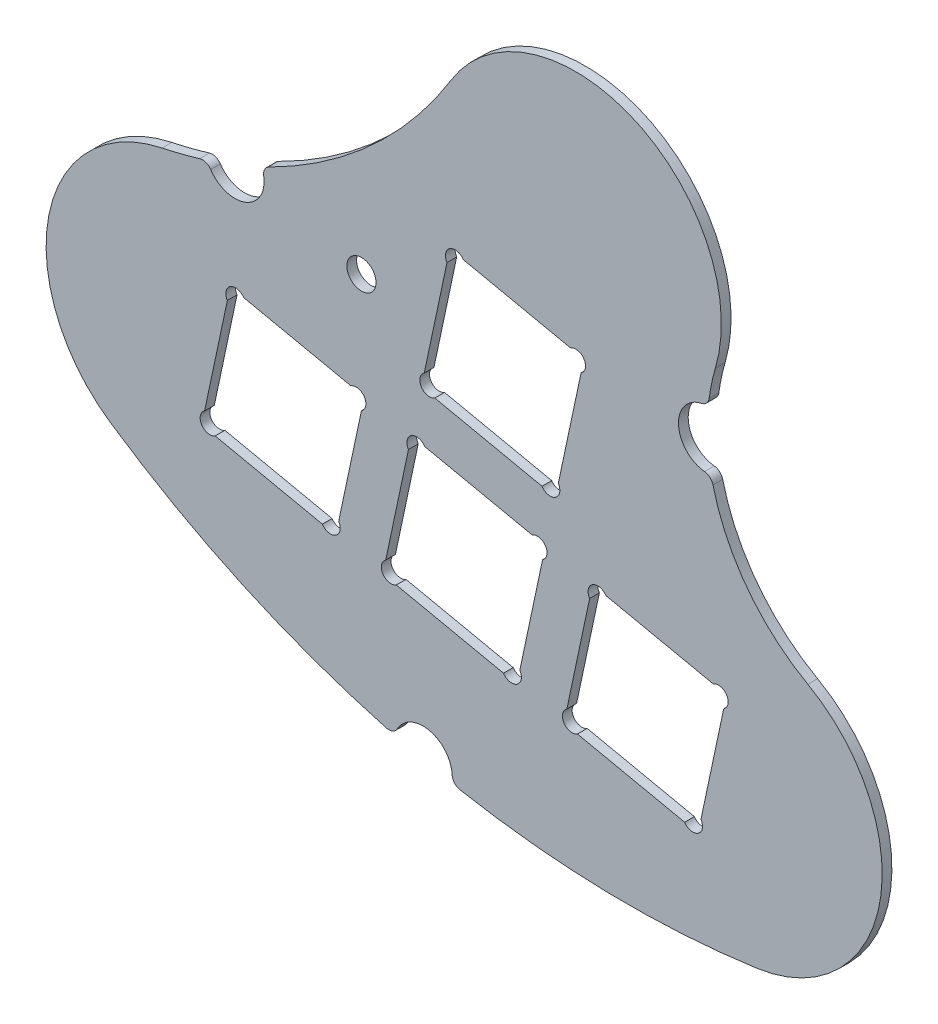
SolidWorks part; units mm, degrees
ref_plane "Front Plane" through (0, 0, 0) normal (0, 0, 1) x (1, 0, 0)
ref_plane "Top Plane" through (0, 0, 0) normal (0, 1, 0) x (1, 0, 0)
ref_plane "Right Plane" through (0, 0, 0) normal (1, 0, 0) x (0, 0, -1)
sketch "Sketch1" plane through (0, 0, 0) normal (0, 0, 1) x (1, 0, 0)
  line L0 (157.8919, 26.2701) -> (191.7747, 29.0915)
  line L1 (157.8919, 26.2701) -> (191.7747, 26.2701)
  line L2 (157.8919, 26.2701) -> (157.8919, 29.0915)
  line L3 (157.8919, 29.0915) -> (191.7747, 29.0915)
  line L4 (191.7747, 26.2701) -> (191.7747, 29.0915)
  line L5 (123.8919, 26.2701) -> (90.0092, 26.2701)
  line L6 (123.8919, 26.2701) -> (123.8919, 29.0915)
  line L7 (123.8919, 29.0915) -> (90.0092, 29.0915)
  line L8 (90.0092, 26.2701) -> (90.0092, 29.0915)
  line L9 (90.0092, 29.0915) -> (123.8919, 26.2701)
  line L10 (168.0919, 58.3601) -> (194.8735, 70.7292)
  line L11 (168.0919, 58.3601) -> (194.8735, 58.3601)
  line L12 (168.0919, 58.3601) -> (168.0919, 70.7292)
  line L13 (168.0919, 70.7292) -> (194.8735, 70.7292)
  line L14 (194.8735, 58.3601) -> (194.8735, 70.7292)
  line L15 (194.8735, 70.7292) -> (224.3587, 70.7292)
  line L16 (194.8735, 70.7292) -> (194.8735, 69.7923)
  line L17 (194.8735, 69.7923) -> (224.3587, 69.7923)
  line L18 (224.3587, 70.7292) -> (224.3587, 69.7923)
  line L19 (224.3587, 69.7923) -> (253.5106, 69.7923)
  line L20 (224.3587, 69.7923) -> (224.3587, 65.2742)
  line L21 (224.3587, 65.2742) -> (253.5106, 65.2742)
  line L22 (253.5106, 69.7923) -> (253.5106, 65.2742)
  line L23 (224.3587, 69.7923) -> (194.8735, 70.7292)
  line L24 (253.5106, 65.2742) -> (224.3587, 69.7923)
  line L25 (170.7502, 87.7401) -> (168.0919, 58.3601)
  line L26 (168.0919, 58.3601) -> (170.7502, 58.3601)
  line L27 (168.0919, 58.3601) -> (168.0919, 87.7401)
  line L28 (168.0919, 87.7401) -> (170.7502, 87.7401)
  line L29 (170.7502, 58.3601) -> (170.7502, 87.7401)
  line L30 (52.9966, 89.4705) -> (24.4119, 82.1791)
  line L31 (24.4119, 82.1791) -> (52.9966, 82.1791)
  line L32 (24.4119, 82.1791) -> (24.4119, 89.4705)
  line L33 (24.4119, 89.4705) -> (52.9966, 89.4705)
  line L34 (52.9966, 82.1791) -> (52.9966, 89.4705)
  line L35 (82.4966, 89.4705) -> (109.0019, 89.4705)
  line L36 (82.4966, 89.4705) -> (82.4966, 76.5201)
  line L37 (82.4966, 76.5201) -> (109.0019, 76.5201)
  line L38 (109.0019, 89.4705) -> (109.0019, 76.5201)
  line L39 (92.4554, 117.2387) -> (82.4966, 117.2387)
  line L40 (92.4554, 117.2387) -> (92.4554, 89.4705)
  line L41 (92.4554, 89.4705) -> (82.4966, 89.4705)
  line L42 (82.4966, 117.2387) -> (82.4966, 89.4705)
  line L43 (92.4554, 117.2387) -> (82.4966, 89.4705)
  line L44 (109.0019, 76.5201) -> (82.4966, 89.4705)
  circle A0 centre (123.8919, 26.2701) radius 14.25
  circle A1 centre (157.8919, 26.2701) radius 14.25
  circle A2 centre (90.0092, 29.0915) radius 14.25
  circle A3 centre (191.7747, 29.0915) radius 14.25
  circle A4 centre (82.4966, 89.4705) radius 11.25
  circle A5 centre (92.4554, 117.2387) radius 11.25
  circle A6 centre (52.9966, 89.4705) radius 11.25
  circle A7 centre (109.0019, 76.5201) radius 11.25
  circle A8 centre (24.4119, 82.1791) radius 11.25
  circle A9 centre (170.7502, 87.7401) radius 11.25
  circle A10 centre (168.0919, 58.3601) radius 11.25
  circle A11 centre (197.5318, 100.1092) radius 11.25
  circle A12 centre (194.8735, 70.7292) radius 11.25
  circle A13 centre (227.0169, 99.1723) radius 11.25
  circle A14 centre (224.3587, 69.7923) radius 11.25
  circle A15 centre (256.1689, 94.6541) radius 11.25
  circle A16 centre (253.5106, 65.2742) radius 11.25
  circle A17 centre (24.4119, 82.1791) radius 12
  circle A18 centre (52.9966, 89.4705) radius 12
  circle A19 centre (92.4554, 117.2387) radius 12
  circle A20 centre (82.4966, 89.4705) radius 12
  circle A21 centre (109.0019, 76.5201) radius 12
  circle A22 centre (168.0919, 58.3601) radius 12
  circle A23 centre (194.8735, 70.7292) radius 12
  circle A24 centre (224.3587, 69.7923) radius 12
  circle A25 centre (253.5106, 65.2742) radius 12
  circle A26 centre (256.1689, 94.6541) radius 12
  circle A27 centre (227.0169, 99.1723) radius 12
  circle A28 centre (197.5318, 100.1092) radius 12
  circle A29 centre (170.7502, 87.7401) radius 12
  circle A30 centre (191.7747, 29.0915) radius 15
  circle A31 centre (157.8919, 26.2701) radius 15
  circle A32 centre (123.8919, 26.2701) radius 15
  circle A33 centre (90.0092, 29.0915) radius 15
  circle A34 centre (173.429, 117.1182) radius 11.25
  circle A35 centre (173.429, 117.1182) radius 12
  dimension "D1" = 28.5
  dimension "D2" = 22.5
  dimension "D3" = 0.75
  dimension "D4" = 0.75
  dimension "D34" = 34
  dimension "D5" = 29.5
  dimension "D6" = 29.5
  dimension "D7" = 29.5
  dimension "D8" = 29.5
  dimension "D9" = 29.5
  dimension "D10" = 29.5
  dimension "D11" = 29.5
  dimension "D12" = 29.5
  dimension "D13" = 29.5
  dimension "D14" = 29.5
  dimension "D15" = 29.5
  dimension "D16" = 29.5
  dimension "D17" = 29.5
  dimension "D18" = 29.5
  dimension "D19" = 34
  dimension "D20" = 34
  dimension "D21" = 32.09
  dimension "D22" = 10.2
  dimension "D23" = 4.76
  dimension "D24" = 4.76
  dimension "D25" = 24.79
  dimension "D26" = 1.82
  dimension "D27" = 8.81
  dimension "D28" = 84.83
  dimension "D29" = 75.69
  dimension "D30" = 70.27
  dimension "D31" = 26.04
  dimension "D32" = 14.89
  dimension "D33" = 50.25
  dimension "D35" = 29.5
  dimension "D36" = 29.5
sketch "Sketch4" plane through (-30.2083, 20.075, 0) normal (0, 0, 1) x (0.9781, -0.2079, 0)
  line L0 (86.1706, 94.1917) -> (105.2206, 75.1417)
  line L1 (67.1206, 94.1917) -> (86.1706, 94.1917)
  line L2 (67.1206, 94.1917) -> (67.1206, 75.1417)
  line L3 (67.1206, 75.1417) -> (86.1706, 75.1417)
  line L4 (86.1706, 94.1917) -> (86.1706, 75.1417)
  line L5 (86.1706, 94.1917) -> (105.2206, 94.1917)
  line L6 (86.1706, 94.1917) -> (86.1706, 75.1417)
  line L7 (86.1706, 75.1417) -> (105.2206, 75.1417)
  line L8 (105.2206, 94.1917) -> (105.2206, 75.1417)
  line L9 (105.2206, 94.1917) -> (124.2706, 94.1917)
  line L10 (105.2206, 94.1917) -> (105.2206, 75.1417)
  line L11 (105.2206, 75.1417) -> (124.2706, 75.1417)
  line L12 (124.2706, 94.1917) -> (124.2706, 75.1417)
  line L13 (86.1706, 94.1917) -> (105.2206, 94.1917)
  line L14 (86.1706, 94.1917) -> (86.1706, 113.2417)
  line L15 (86.1706, 113.2417) -> (105.2206, 113.2417)
  line L16 (105.2206, 94.1917) -> (105.2206, 113.2417)
  line L17 (66.9585, 85.1784) -> (124.4326, 84.1551)
  point P14 (95.6956, 84.6667)
  point P15 (95.6956, 84.6667)
  dimension "D1" = 19.05
sketch "Sketch9" plane through (0, 0, 0) normal (0, 0, 1) x (1, 0, 0)
  line L1 (17.3619, 89.2291) -> (31.4619, 89.2291)
  line L2 (17.3619, 89.2291) -> (17.3619, 75.1291)
  line L3 (17.3619, 75.1291) -> (31.4619, 75.1291)
  line L4 (31.4619, 89.2291) -> (31.4619, 75.1291)
  line L5 (45.9466, 96.5205) -> (60.0466, 96.5205)
  line L6 (45.9466, 96.5205) -> (45.9466, 82.4205)
  line L7 (45.9466, 82.4205) -> (60.0466, 82.4205)
  line L8 (60.0466, 96.5205) -> (60.0466, 82.4205)
  line L9 (75.4466, 96.5205) -> (89.5466, 96.5205)
  line L10 (75.4466, 96.5205) -> (75.4466, 82.4205)
  line L11 (75.4466, 82.4205) -> (89.5466, 82.4205)
  line L12 (89.5466, 96.5205) -> (89.5466, 82.4205)
  line L13 (101.9519, 83.5701) -> (116.0519, 83.5701)
  line L14 (101.9519, 83.5701) -> (101.9519, 69.4701)
  line L15 (101.9519, 69.4701) -> (116.0519, 69.4701)
  line L16 (116.0519, 83.5701) -> (116.0519, 69.4701)
  line L17 (85.4054, 124.2887) -> (99.5054, 124.2887)
  line L18 (85.4054, 124.2887) -> (85.4054, 110.1887)
  line L19 (85.4054, 110.1887) -> (99.5054, 110.1887)
  line L20 (99.5054, 124.2887) -> (99.5054, 110.1887)
  line L21 (82.9592, 36.1415) -> (97.0592, 36.1415)
  line L22 (82.9592, 36.1415) -> (82.9592, 22.0415)
  line L23 (82.9592, 22.0415) -> (97.0592, 22.0415)
  line L24 (97.0592, 36.1415) -> (97.0592, 22.0415)
  line L25 (116.8419, 33.3201) -> (130.9419, 33.3201)
  line L26 (116.8419, 33.3201) -> (116.8419, 19.2201)
  line L27 (116.8419, 19.2201) -> (130.9419, 19.2201)
  line L28 (130.9419, 33.3201) -> (130.9419, 19.2201)
  line L29 (150.8419, 33.3201) -> (164.9419, 33.3201)
  line L30 (150.8419, 33.3201) -> (150.8419, 19.2201)
  line L31 (150.8419, 19.2201) -> (164.9419, 19.2201)
  line L32 (164.9419, 33.3201) -> (164.9419, 19.2201)
  line L33 (184.7247, 36.1415) -> (198.8247, 36.1415)
  line L34 (184.7247, 36.1415) -> (184.7247, 22.0415)
  line L35 (184.7247, 22.0415) -> (198.8247, 22.0415)
  line L36 (198.8247, 36.1415) -> (198.8247, 22.0415)
  line L37 (260.5606, 58.2242) -> (246.4606, 58.2242)
  line L38 (260.5606, 58.2242) -> (260.5606, 72.3242)
  line L39 (260.5606, 72.3242) -> (246.4606, 72.3242)
  line L40 (246.4606, 58.2242) -> (246.4606, 72.3242)
  line L41 (217.3087, 76.8423) -> (231.4087, 76.8423)
  line L42 (217.3087, 76.8423) -> (217.3087, 62.7423)
  line L43 (217.3087, 62.7423) -> (231.4087, 62.7423)
  line L44 (231.4087, 76.8423) -> (231.4087, 62.7423)
  line L45 (187.8235, 77.7792) -> (201.9235, 77.7792)
  line L46 (187.8235, 77.7792) -> (187.8235, 63.6792)
  line L47 (187.8235, 63.6792) -> (201.9235, 63.6792)
  line L48 (201.9235, 77.7792) -> (201.9235, 63.6792)
  line L49 (161.0419, 65.4101) -> (175.1419, 65.4101)
  line L50 (161.0419, 65.4101) -> (161.0419, 51.3101)
  line L51 (161.0419, 51.3101) -> (175.1419, 51.3101)
  line L52 (175.1419, 65.4101) -> (175.1419, 51.3101)
  line L53 (163.7002, 94.7901) -> (177.8002, 94.7901)
  line L54 (163.7002, 94.7901) -> (163.7002, 80.6901)
  line L55 (163.7002, 80.6901) -> (177.8002, 80.6901)
  line L56 (177.8002, 94.7901) -> (177.8002, 80.6901)
  line L57 (190.4818, 107.1592) -> (204.5818, 107.1592)
  line L58 (190.4818, 107.1592) -> (190.4818, 93.0592)
  line L59 (190.4818, 93.0592) -> (204.5818, 93.0592)
  line L60 (204.5818, 107.1592) -> (204.5818, 93.0592)
  line L61 (219.9669, 106.2223) -> (234.0669, 106.2223)
  line L62 (219.9669, 106.2223) -> (219.9669, 92.1223)
  line L63 (219.9669, 92.1223) -> (234.0669, 92.1223)
  line L64 (234.0669, 106.2223) -> (234.0669, 92.1223)
  line L65 (249.1189, 101.7041) -> (263.2189, 101.7041)
  line L66 (249.1189, 101.7041) -> (249.1189, 87.6041)
  line L67 (249.1189, 87.6041) -> (263.2189, 87.6041)
  line L68 (263.2189, 101.7041) -> (263.2189, 87.6041)
  line L69 (166.379, 124.1682) -> (180.479, 124.1682)
  line L70 (166.379, 124.1682) -> (166.379, 110.0682)
  line L71 (166.379, 110.0682) -> (180.479, 110.0682)
  line L72 (180.479, 124.1682) -> (180.479, 110.0682)
  point P72 (24.4119, 89.2291)
  point P74 (52.9966, 96.5205)
  point P76 (82.4966, 96.5205)
  point P78 (92.4554, 124.2887)
  point P80 (109.0019, 83.5701)
  point P82 (90.0092, 36.1415)
  point P84 (123.8919, 33.3201)
  point P86 (157.8919, 33.3201)
  point P88 (191.7747, 36.1415)
  point P90 (168.0919, 65.4101)
  point P92 (170.7502, 94.7901)
  point P94 (173.429, 124.1682)
  point P96 (197.5318, 107.1592)
  point P98 (227.0169, 106.2223)
  point P100 (256.1689, 101.7041)
  point P102 (194.8735, 77.7792)
  point P104 (224.3587, 76.8423)
  point P106 (253.5106, 72.3242)
  point P108 (17.3619, 82.1791)
  point P109 (45.9466, 89.4705)
  point P110 (75.4466, 89.4705)
  point P111 (101.9519, 76.5201)
  point P112 (85.4054, 117.2387)
  point P113 (82.9592, 29.0915)
  point P114 (116.8419, 26.2701)
  point P115 (150.8419, 26.2701)
  point P116 (184.7247, 29.0915)
  point P118 (161.0419, 58.3601)
  point P119 (187.8235, 70.7292)
  point P120 (217.3087, 69.7923)
  point P121 (246.4606, 65.2742)
  point P122 (163.7002, 87.7401)
  point P123 (190.4818, 100.1092)
  point P124 (219.9669, 99.1723)
  point P125 (249.1189, 94.6541)
  point P126 (166.379, 117.1182)
  dimension "D1" = 14.1
sketch "Sketch10" plane through (-22.0981, 19.3454, 0) normal (0, 0, 1) x (0.9781, -0.2079, 0)
  line L1 (61.5108, 90.7441) -> (75.6108, 90.7441)
  line L2 (61.5108, 90.7441) -> (61.5108, 76.6441)
  line L3 (61.5108, 76.6441) -> (75.6108, 76.6441)
  line L4 (75.6108, 90.7441) -> (75.6108, 76.6441)
  line L5 (80.5608, 90.7441) -> (94.6608, 90.7441)
  line L6 (80.5608, 90.7441) -> (80.5608, 76.6441)
  line L7 (80.5608, 76.6441) -> (94.6608, 76.6441)
  line L8 (94.6608, 90.7441) -> (94.6608, 76.6441)
  line L9 (99.6108, 90.7441) -> (113.7108, 90.7441)
  line L10 (99.6108, 90.7441) -> (99.6108, 76.6441)
  line L11 (99.6108, 76.6441) -> (113.7108, 76.6441)
  line L12 (113.7108, 90.7441) -> (113.7108, 76.6441)
  line L13 (80.5608, 109.7941) -> (94.6608, 109.7941)
  line L14 (80.5608, 109.7941) -> (80.5608, 95.6941)
  line L15 (80.5608, 95.6941) -> (94.6608, 95.6941)
  line L16 (94.6608, 109.7941) -> (94.6608, 95.6941)
  line L17 (50.5121, 89.6359) -> (53.4436, 75.8441) construction
  line L18 (59.0358, 93.2191) -> (78.0858, 93.2191) construction
  line L19 (78.0858, 112.2691) -> (97.1358, 112.2691) construction
  line L20 (97.1358, 93.2191) -> (116.1858, 93.2191) construction
  line L21 (78.0858, 93.2191) -> (78.0858, 112.2691) construction
  line L23 (59.0358, 93.2191) -> (59.0358, 74.1691) construction
  point P16 (75.6108, 83.6941)
  point P17 (94.6608, 83.6941)
  point P18 (113.7108, 83.6941)
  point P19 (87.6108, 90.7441)
  point P20 (87.6108, 109.7941)
  point P23 (68.5608, 90.7441)
  point P26 (68.5608, 93.2191)
  point P29 (87.6108, 112.2691)
  point P30 (106.6608, 90.7441)
  point P33 (106.6608, 93.2191)
  point P34 (80.5608, 102.7441)
  point P37 (78.0858, 102.7441)
  point P42 (59.0358, 83.6941)
  point P43 (61.5108, 83.6941)
sketch "Sketch14" plane through (0, 0, 0) normal (0, 0, 1) x (1, 0, 0)
  line L0 (165.1144, 80.6901) -> (163.7002, 82.1043)
  line L1 (163.7002, 93.3758) -> (165.1144, 94.7901)
  line L2 (177.8002, 93.3758) -> (176.386, 94.7901)
  line L3 (179.0648, 110.0682) -> (180.479, 111.4824)
  line L4 (166.379, 111.4824) -> (167.7932, 110.0682)
  line L5 (166.379, 122.754) -> (167.7932, 124.1682)
  line L6 (179.0648, 124.1682) -> (180.479, 122.754)
  line L7 (203.1676, 93.0592) -> (204.5818, 94.4734)
  line L8 (17.3619, 89.2291) -> (17.3619, 75.1291) construction
  line L9 (17.3619, 89.2291) -> (31.4619, 89.2291) construction
  line L10 (17.3619, 87.8149) -> (18.7761, 89.2291)
  line L11 (17.3619, 75.1291) -> (31.4619, 75.1291) construction
  line L12 (31.4619, 89.2291) -> (31.4619, 75.1291) construction
  line L13 (45.9466, 96.5205) -> (60.0466, 96.5205) construction
  line L14 (60.0466, 96.5205) -> (60.0466, 82.4205) construction
  line L15 (45.9466, 96.5205) -> (45.9466, 82.4205) construction
  line L16 (45.9466, 82.4205) -> (60.0466, 82.4205) construction
  line L17 (85.4054, 124.2887) -> (85.4054, 110.1887) construction
  line L18 (85.4054, 124.2887) -> (99.5054, 124.2887) construction
  line L19 (99.5054, 124.2887) -> (99.5054, 110.1887) construction
  line L20 (85.4054, 110.1887) -> (99.5054, 110.1887) construction
  line L21 (101.9519, 83.5701) -> (101.9519, 69.4701) construction
  line L22 (101.9519, 83.5701) -> (116.0519, 83.5701) construction
  line L23 (116.0519, 83.5701) -> (116.0519, 69.4701) construction
  line L24 (101.9519, 69.4701) -> (116.0519, 69.4701) construction
  line L25 (91.2712, 73.6044) -> (105.0631, 70.6729) construction
  line L26 (107.9947, 84.4647) -> (105.0631, 70.6729) construction
  line L27 (94.2028, 87.3963) -> (107.9947, 84.4647) construction
  line L28 (94.2028, 87.3963) -> (91.2712, 73.6044) construction
  line L29 (72.6375, 77.5651) -> (86.4294, 74.6336) construction
  line L30 (89.361, 88.4255) -> (86.4294, 74.6336) construction
  line L31 (75.5691, 91.357) -> (89.361, 88.4255) construction
  line L32 (75.5691, 91.357) -> (72.6375, 77.5651) construction
  line L33 (56.9354, 95.3177) -> (54.0038, 81.5259) construction
  line L34 (56.9354, 95.3177) -> (70.7273, 92.3862) construction
  line L35 (70.7273, 92.3862) -> (67.7957, 78.5943) construction
  line L36 (54.0038, 81.5259) -> (67.7957, 78.5943) construction
  line L37 (76.5983, 96.1988) -> (90.3901, 93.2673) construction
  line L38 (93.3217, 107.0592) -> (90.3901, 93.2673) construction
  line L39 (79.5298, 109.9907) -> (76.5983, 96.1988) construction
  line L40 (79.5298, 109.9907) -> (93.3217, 107.0592) construction
  line L41 (82.9592, 36.1415) -> (82.9592, 22.0415) construction
  line L42 (82.9592, 36.1415) -> (97.0592, 36.1415) construction
  line L43 (82.9592, 22.0415) -> (97.0592, 22.0415) construction
  line L44 (97.0592, 36.1415) -> (97.0592, 22.0415) construction
  line L45 (116.8419, 33.3201) -> (116.8419, 19.2201) construction
  line L46 (116.8419, 33.3201) -> (130.9419, 33.3201) construction
  line L47 (116.8419, 19.2201) -> (130.9419, 19.2201) construction
  line L48 (130.9419, 33.3201) -> (130.9419, 19.2201) construction
  line L49 (150.8419, 33.3201) -> (150.8419, 19.2201) construction
  line L50 (150.8419, 33.3201) -> (164.9419, 33.3201) construction
  line L51 (164.9419, 33.3201) -> (164.9419, 19.2201) construction
  line L52 (150.8419, 19.2201) -> (164.9419, 19.2201) construction
  line L53 (184.7247, 36.1415) -> (184.7247, 22.0415) construction
  line L54 (184.7247, 22.0415) -> (198.8247, 22.0415) construction
  line L55 (198.8247, 36.1415) -> (198.8247, 22.0415) construction
  line L56 (184.7247, 36.1415) -> (198.8247, 36.1415) construction
  line L57 (161.0419, 65.4101) -> (175.1419, 65.4101) construction
  line L58 (175.1419, 65.4101) -> (175.1419, 51.3101) construction
  line L59 (161.0419, 51.3101) -> (175.1419, 51.3101) construction
  line L60 (161.0419, 65.4101) -> (161.0419, 51.3101) construction
  line L61 (187.8235, 77.7792) -> (187.8235, 63.6792) construction
  line L62 (187.8235, 77.7792) -> (201.9235, 77.7792) construction
  line L63 (187.8235, 63.6792) -> (201.9235, 63.6792) construction
  line L64 (201.9235, 77.7792) -> (201.9235, 63.6792) construction
  line L65 (217.3087, 76.8423) -> (217.3087, 62.7423) construction
  line L66 (217.3087, 76.8423) -> (231.4087, 76.8423) construction
  line L67 (231.4087, 76.8423) -> (231.4087, 62.7423) construction
  line L68 (217.3087, 62.7423) -> (231.4087, 62.7423) construction
  line L69 (260.5606, 58.2242) -> (246.4606, 58.2242) construction
  line L70 (260.5606, 58.2242) -> (260.5606, 72.3242) construction
  line L71 (246.4606, 58.2242) -> (246.4606, 72.3242) construction
  line L72 (260.5606, 72.3242) -> (246.4606, 72.3242) construction
  line L73 (249.1189, 101.7041) -> (263.2189, 101.7041) construction
  line L74 (263.2189, 101.7041) -> (263.2189, 87.6041) construction
  line L75 (249.1189, 87.6041) -> (263.2189, 87.6041) construction
  line L76 (249.1189, 101.7041) -> (249.1189, 87.6041) construction
  line L77 (219.9669, 106.2223) -> (219.9669, 92.1223) construction
  line L78 (219.9669, 106.2223) -> (234.0669, 106.2223) construction
  line L79 (234.0669, 106.2223) -> (234.0669, 92.1223) construction
  line L80 (219.9669, 92.1223) -> (234.0669, 92.1223) construction
  line L81 (190.4818, 107.1592) -> (204.5818, 107.1592) construction
  line L82 (204.5818, 107.1592) -> (204.5818, 93.0592) construction
  line L83 (190.4818, 93.0592) -> (204.5818, 93.0592) construction
  line L84 (190.4818, 107.1592) -> (190.4818, 93.0592) construction
  line L85 (163.7002, 94.7901) -> (177.8002, 94.7901) construction
  line L86 (177.8002, 94.7901) -> (177.8002, 80.6901) construction
  line L87 (163.7002, 80.6901) -> (177.8002, 80.6901) construction
  line L88 (163.7002, 94.7901) -> (163.7002, 80.6901) construction
  line L89 (180.479, 124.1682) -> (180.479, 110.0682) construction
  line L90 (166.379, 110.0682) -> (180.479, 110.0682) construction
  line L91 (166.379, 124.1682) -> (166.379, 110.0682) construction
  line L92 (166.379, 124.1682) -> (180.479, 124.1682) construction
  line L93 (17.3619, 76.5433) -> (18.7761, 75.1291)
  line L94 (30.0477, 75.1291) -> (31.4619, 76.5433)
  line L95 (31.4619, 87.8149) -> (30.0477, 89.2291)
  line L96 (45.9466, 95.1063) -> (47.3608, 96.5205)
  line L97 (45.9466, 83.8347) -> (47.3608, 82.4205)
  line L98 (54.2979, 82.9092) -> (55.3871, 81.2318)
  line L99 (58.6323, 82.4205) -> (60.0466, 83.8347)
  line L100 (56.6413, 93.9344) -> (58.3187, 95.0237)
  line L101 (58.6323, 96.5205) -> (60.0466, 95.1063)
  line L102 (69.3439, 92.6802) -> (70.4332, 91.0029)
  line L103 (68.0897, 79.9776) -> (66.4124, 78.8883)
  line L104 (75.2751, 89.9737) -> (76.9524, 91.063)
  line L105 (72.9316, 78.9484) -> (74.0208, 77.2711)
  line L106 (85.0461, 74.9276) -> (86.7234, 76.0169)
  line L107 (89.0669, 87.0421) -> (87.9777, 88.7195)
  line L108 (89.0068, 93.5613) -> (90.6842, 94.6506)
  line L109 (76.8923, 97.5822) -> (77.9816, 95.9048)
  line L110 (91.9384, 107.3532) -> (93.0277, 105.6759)
  line L111 (79.2358, 108.6074) -> (80.9131, 109.6967)
  line L112 (85.4054, 111.6029) -> (86.8196, 110.1887)
  line L113 (98.0912, 110.1887) -> (99.5054, 111.6029)
  line L114 (98.0912, 124.2887) -> (99.5054, 122.8745)
  line L115 (85.4054, 122.8745) -> (86.8196, 124.2887)
  line L116 (93.9088, 86.013) -> (95.5861, 87.1023)
  line L117 (91.5653, 74.9877) -> (92.6546, 73.3104)
  line L118 (103.6798, 70.9669) -> (105.3572, 72.0562)
  line L119 (106.6114, 84.7588) -> (107.7006, 83.0814)
  line L120 (101.9519, 82.1559) -> (103.3662, 83.5701)
  line L121 (101.9519, 70.8843) -> (103.3662, 69.4701)
  line L122 (114.6377, 69.4701) -> (116.0519, 70.8843)
  line L123 (116.0519, 82.1559) -> (114.6377, 83.5701)
  line L124 (82.9592, 34.7272) -> (84.3734, 36.1415)
  line L125 (82.9592, 23.4557) -> (84.3734, 22.0415)
  line L126 (95.645, 22.0415) -> (97.0592, 23.4557)
  line L127 (97.0592, 34.7272) -> (95.645, 36.1415)
  line L128 (116.8419, 31.9059) -> (118.2562, 33.3201)
  line L129 (116.8419, 20.6343) -> (118.2562, 19.2201)
  line L130 (129.5277, 19.2201) -> (130.9419, 20.6343)
  line L131 (130.9419, 31.9059) -> (129.5277, 33.3201)
  line L132 (150.8419, 31.9059) -> (152.2562, 33.3201)
  line L133 (150.8419, 20.6343) -> (152.2562, 19.2201)
  line L134 (163.5277, 19.2201) -> (164.9419, 20.6343)
  line L135 (164.9419, 31.9059) -> (163.5277, 33.3201)
  line L136 (184.7247, 34.7272) -> (186.1389, 36.1415)
  line L137 (184.7247, 23.4557) -> (186.1389, 22.0415)
  line L138 (197.4105, 22.0415) -> (198.8247, 23.4557)
  line L139 (198.8247, 34.7272) -> (197.4105, 36.1415)
  line L140 (173.7277, 51.3101) -> (175.1419, 52.7243)
  line L141 (161.0419, 52.7243) -> (162.4562, 51.3101)
  line L142 (161.0419, 63.9959) -> (162.4562, 65.4101)
  line L143 (173.7277, 65.4101) -> (175.1419, 63.9959)
  line L144 (187.8235, 65.0934) -> (189.2378, 63.6792)
  line L145 (200.5093, 63.6792) -> (201.9235, 65.0934)
  line L146 (200.5093, 77.7792) -> (201.9235, 76.365)
  line L147 (187.8235, 76.365) -> (189.2378, 77.7792)
  line L148 (176.386, 80.6901) -> (177.8002, 82.1043)
  line L149 (204.5818, 105.745) -> (203.1676, 107.1592)
  line L150 (191.896, 107.1592) -> (190.4818, 105.745)
  line L151 (190.4818, 94.4734) -> (191.896, 93.0592)
  line L152 (219.9669, 104.8081) -> (221.3812, 106.2223)
  line L153 (232.6527, 106.2223) -> (234.0669, 104.8081)
  line L154 (234.0669, 93.5365) -> (232.6527, 92.1223)
  line L155 (219.9669, 93.5365) -> (221.3812, 92.1223)
  line L156 (229.9944, 76.8423) -> (231.4087, 75.4281)
  line L157 (217.3087, 75.4281) -> (218.7229, 76.8423)
  line L158 (217.3087, 64.1565) -> (218.7229, 62.7423)
  line L159 (229.9944, 62.7423) -> (231.4087, 64.1565)
  line L160 (259.1464, 72.3242) -> (260.5606, 70.9099)
  line L161 (246.4606, 70.9099) -> (247.8748, 72.3242)
  line L162 (259.1464, 58.2242) -> (260.5606, 59.6384)
  line L163 (247.8748, 58.2242) -> (246.4606, 59.6384)
  line L164 (261.8047, 87.6041) -> (263.2189, 89.0183)
  line L165 (249.1189, 89.0183) -> (250.5331, 87.6041)
  line L166 (249.1189, 100.2899) -> (250.5331, 101.7041)
  line L167 (261.8047, 101.7041) -> (263.2189, 100.2899)
  line L168 (75.4466, 96.5205) -> (75.4466, 82.4205) construction
  line L169 (75.4466, 96.5205) -> (89.5466, 96.5205) construction
  line L170 (89.5466, 96.5205) -> (89.5466, 82.4205) construction
  line L171 (75.4466, 82.4205) -> (89.5466, 82.4205) construction
  line L172 (76.8608, 96.5205) -> (75.4466, 95.1063)
  line L173 (88.1323, 96.5205) -> (89.5466, 95.1063)
  line L174 (89.5466, 83.8347) -> (88.1323, 82.4205)
  line L175 (75.4466, 83.8347) -> (76.8608, 82.4205)
  arc A0 (17.3619, 87.8149) -> (18.7761, 89.2291) centre (18.069, 88.522) cw
  arc A1 (18.7761, 75.1291) -> (17.3619, 76.5433) centre (18.069, 75.8362) cw
  arc A2 (31.4619, 76.5433) -> (30.0477, 75.1291) centre (30.7548, 75.8362) cw
  arc A3 (30.0477, 89.2291) -> (31.4619, 87.8149) centre (30.7548, 88.522) cw
  arc A4 (58.6323, 96.5205) -> (60.0466, 95.1063) centre (59.3394, 95.8134) cw
  arc A5 (45.9466, 95.1063) -> (47.3608, 96.5205) centre (46.6537, 95.8134) cw
  arc A6 (47.3608, 82.4205) -> (45.9466, 83.8347) centre (46.6537, 83.1276) cw
  arc A7 (60.0466, 83.8347) -> (58.6323, 82.4205) centre (59.3394, 83.1276) cw
  arc A8 (85.4054, 122.8745) -> (86.8196, 124.2887) centre (86.1125, 123.5816) cw
  arc A9 (98.0912, 124.2887) -> (99.5054, 122.8745) centre (98.7983, 123.5816) cw
  arc A10 (99.5054, 111.6029) -> (98.0912, 110.1887) centre (98.7983, 110.8958) cw
  arc A11 (85.4054, 111.6029) -> (86.8196, 110.1887) centre (86.1125, 110.8958) ccw
  arc A12 (101.9519, 82.1559) -> (103.3662, 83.5701) centre (102.6591, 82.863) cw
  arc A13 (114.6377, 83.5701) -> (116.0519, 82.1559) centre (115.3448, 82.863) cw
  arc A14 (116.0519, 70.8843) -> (114.6377, 69.4701) centre (115.3448, 70.1772) cw
  arc A15 (101.9519, 70.8843) -> (103.3662, 69.4701) centre (102.6591, 70.1772) ccw
  arc A16 (103.6798, 70.9669) -> (105.3572, 72.0562) centre (104.5185, 71.5115) ccw
  arc A17 (106.6114, 84.7588) -> (107.7006, 83.0814) centre (107.156, 83.9201) cw
  arc A18 (93.9088, 86.013) -> (95.5861, 87.1023) centre (94.7474, 86.5576) cw
  arc A19 (91.5653, 74.9877) -> (92.6546, 73.3104) centre (92.1099, 74.1491) ccw
  arc A20 (85.0461, 74.9276) -> (86.7234, 76.0169) centre (85.8848, 75.4722) ccw
  arc A21 (87.9777, 88.7195) -> (89.0669, 87.0421) centre (88.5223, 87.8808) cw
  arc A22 (75.2751, 89.9737) -> (76.9524, 91.063) centre (76.1137, 90.5183) cw
  arc A23 (72.9316, 78.9484) -> (74.0208, 77.2711) centre (73.4762, 78.1098) ccw
  arc A24 (56.6413, 93.9344) -> (58.3187, 95.0237) centre (57.48, 94.4791) cw
  arc A25 (69.3439, 92.6802) -> (70.4332, 91.0029) centre (69.8886, 91.8415) cw
  arc A26 (68.0897, 79.9776) -> (66.4124, 78.8883) centre (67.2511, 79.433) cw
  arc A27 (54.2979, 82.9092) -> (55.3871, 81.2318) centre (54.8425, 82.0705) ccw
  arc A28 (89.0068, 93.5613) -> (90.6842, 94.6506) centre (89.8455, 94.106) ccw
  arc A29 (76.8923, 97.5822) -> (77.9816, 95.9048) centre (77.4369, 96.7435) ccw
  arc A30 (79.2358, 108.6074) -> (80.9131, 109.6967) centre (80.0744, 109.1521) cw
  arc A31 (91.9384, 107.3532) -> (93.0277, 105.6759) centre (92.483, 106.5145) cw
  arc A32 (82.9592, 34.7272) -> (84.3734, 36.1415) centre (83.6663, 35.4344) cw
  arc A33 (82.9592, 23.4557) -> (84.3734, 22.0415) centre (83.6663, 22.7486) ccw
  arc A34 (95.645, 22.0415) -> (97.0592, 23.4557) centre (96.3521, 22.7486) ccw
  arc A35 (95.645, 36.1415) -> (97.0592, 34.7272) centre (96.3521, 35.4344) cw
  arc A36 (116.8419, 31.9059) -> (118.2562, 33.3201) centre (117.5491, 32.613) cw
  arc A37 (116.8419, 20.6343) -> (118.2562, 19.2201) centre (117.5491, 19.9272) ccw
  arc A38 (129.5277, 19.2201) -> (130.9419, 20.6343) centre (130.2348, 19.9272) ccw
  arc A39 (129.5277, 33.3201) -> (130.9419, 31.9059) centre (130.2348, 32.613) cw
  arc A40 (150.8419, 31.9059) -> (152.2562, 33.3201) centre (151.5491, 32.613) cw
  arc A41 (163.5277, 33.3201) -> (164.9419, 31.9059) centre (164.2348, 32.613) cw
  arc A42 (164.9419, 20.6343) -> (163.5277, 19.2201) centre (164.2348, 19.9272) cw
  arc A43 (150.8419, 20.6343) -> (152.2562, 19.2201) centre (151.5491, 19.9272) ccw
  arc A44 (184.7247, 23.4557) -> (186.1389, 22.0415) centre (185.4318, 22.7486) ccw
  arc A45 (197.4105, 22.0415) -> (198.8247, 23.4557) centre (198.1176, 22.7486) ccw
  arc A46 (197.4105, 36.1415) -> (198.8247, 34.7272) centre (198.1176, 35.4344) cw
  arc A47 (184.7247, 34.7272) -> (186.1389, 36.1415) centre (185.4318, 35.4344) cw
  arc A48 (173.7277, 65.4101) -> (175.1419, 63.9959) centre (174.4348, 64.703) cw
  arc A49 (175.1419, 52.7243) -> (173.7277, 51.3101) centre (174.4348, 52.0172) cw
  arc A50 (161.0419, 52.7243) -> (162.4562, 51.3101) centre (161.7491, 52.0172) ccw
  arc A51 (161.0419, 63.9959) -> (162.4562, 65.4101) centre (161.7491, 64.703) cw
  arc A52 (187.8235, 76.365) -> (189.2378, 77.7792) centre (188.5306, 77.0721) cw
  arc A53 (187.8235, 65.0934) -> (189.2378, 63.6792) centre (188.5306, 64.3863) ccw
  arc A54 (200.5093, 63.6792) -> (201.9235, 65.0934) centre (201.2164, 64.3863) ccw
  arc A55 (200.5093, 77.7792) -> (201.9235, 76.365) centre (201.2164, 77.0721) cw
  arc A56 (217.3087, 75.4281) -> (218.7229, 76.8423) centre (218.0158, 76.1352) cw
  arc A57 (229.9944, 76.8423) -> (231.4087, 75.4281) centre (230.7016, 76.1352) cw
  arc A58 (231.4087, 64.1565) -> (229.9944, 62.7423) centre (230.7016, 63.4494) cw
  arc A59 (217.3087, 64.1565) -> (218.7229, 62.7423) centre (218.0158, 63.4494) ccw
  arc A60 (259.1464, 58.2242) -> (260.5606, 59.6384) centre (259.8535, 58.9313) ccw
  arc A61 (246.4606, 59.6384) -> (247.8748, 58.2242) centre (247.1677, 58.9313) ccw
  arc A62 (246.4606, 70.9099) -> (247.8748, 72.3242) centre (247.1677, 71.617) cw
  arc A63 (259.1464, 72.3242) -> (260.5606, 70.9099) centre (259.8535, 71.617) cw
  arc A64 (261.8047, 101.7041) -> (263.2189, 100.2899) centre (262.5118, 100.997) cw
  arc A65 (263.2189, 89.0183) -> (261.8047, 87.6041) centre (262.5118, 88.3112) cw
  arc A66 (250.5331, 87.6041) -> (249.1189, 89.0183) centre (249.826, 88.3112) cw
  arc A67 (249.1189, 100.2899) -> (250.5331, 101.7041) centre (249.826, 100.997) cw
  arc A68 (219.9669, 104.8081) -> (221.3812, 106.2223) centre (220.674, 105.5152) cw
  arc A69 (232.6527, 106.2223) -> (234.0669, 104.8081) centre (233.3598, 105.5152) cw
  arc A70 (234.0669, 93.5365) -> (232.6527, 92.1223) centre (233.3598, 92.8294) cw
  arc A71 (221.3812, 92.1223) -> (219.9669, 93.5365) centre (220.674, 92.8294) cw
  arc A72 (203.1676, 107.1592) -> (204.5818, 105.745) centre (203.8747, 106.4521) cw
  arc A73 (204.5818, 94.4734) -> (203.1676, 93.0592) centre (203.8747, 93.7663) cw
  arc A74 (191.896, 93.0592) -> (190.4818, 94.4734) centre (191.1889, 93.7663) cw
  arc A75 (190.4818, 105.745) -> (191.896, 107.1592) centre (191.1889, 106.4521) cw
  arc A76 (176.386, 94.7901) -> (177.8002, 93.3758) centre (177.0931, 94.0829) cw
  arc A77 (177.8002, 82.1043) -> (176.386, 80.6901) centre (177.0931, 81.3972) cw
  arc A78 (165.1144, 80.6901) -> (163.7002, 82.1043) centre (164.4073, 81.3972) cw
  arc A79 (163.7002, 93.3758) -> (165.1144, 94.7901) centre (164.4073, 94.0829) cw
  arc A80 (180.479, 111.4824) -> (179.0648, 110.0682) centre (179.7719, 110.7753) cw
  arc A81 (167.7932, 110.0682) -> (166.379, 111.4824) centre (167.0861, 110.7753) cw
  arc A82 (179.0648, 124.1682) -> (180.479, 122.754) centre (179.7719, 123.4611) cw
  arc A83 (166.379, 122.754) -> (167.7932, 124.1682) centre (167.0861, 123.4611) cw
  arc A84 (75.4466, 95.1063) -> (76.8608, 96.5205) centre (76.1537, 95.8134) cw
  arc A85 (88.1323, 96.5205) -> (89.5466, 95.1063) centre (88.8394, 95.8134) cw
  arc A86 (89.5466, 83.8347) -> (88.1323, 82.4205) centre (88.8394, 83.1276) cw
  arc A87 (76.8608, 82.4205) -> (75.4466, 83.8347) centre (76.1537, 83.1276) cw
  dimension "D1" = 45
  dimension "D2" = 1
  dimension "D71" = 45
  dimension "D3" = 45
  dimension "D4" = 45
  dimension "D5" = 45
  dimension "D6" = 45
  dimension "D7" = 45
  dimension "D8" = 45
  dimension "D9" = 45
  dimension "D10" = 45
  dimension "D11" = 45
  dimension "D12" = 45
  dimension "D13" = 45
  dimension "D14" = 45
  dimension "D15" = 45
  dimension "D16" = 45
  dimension "D17" = 45
  dimension "D18" = 45
  dimension "D19" = 45
  dimension "D20" = 45
  dimension "D21" = 45
  dimension "D22" = 45
  dimension "D23" = 45
  dimension "D24" = 45
  dimension "D25" = 45
  dimension "D26" = 45
  dimension "D27" = 45
  dimension "D28" = 45
  dimension "D29" = 45
  dimension "D30" = 45
  dimension "D31" = 45
  dimension "D32" = 45
  dimension "D33" = 45
  dimension "D34" = 45
  dimension "D35" = 45
  dimension "D36" = 45
  dimension "D37" = 45
  dimension "D38" = 45
  dimension "D39" = 45
  dimension "D40" = 45
  dimension "D41" = 45
  dimension "D42" = 45
  dimension "D43" = 45
  dimension "D44" = 45
  dimension "D45" = 45
  dimension "D46" = 45
  dimension "D47" = 45
  dimension "D48" = 45
  dimension "D49" = 45
  dimension "D50" = 45
  dimension "D51" = 45
  dimension "D52" = 45
  dimension "D53" = 45
  dimension "D54" = 45
  dimension "D55" = 45
  dimension "D56" = 45
  dimension "D57" = 45
  dimension "D58" = 45
  dimension "D59" = 45
  dimension "D60" = 45
  dimension "D61" = 45
  dimension "D62" = 45
  dimension "D63" = 45
  dimension "D64" = 45
  dimension "D65" = 45
  dimension "D66" = 45
  dimension "D67" = 45
  dimension "D68" = 45
  dimension "D69" = 45
  dimension "D70" = 45
  dimension "D72" = 45
  dimension "D73" = 45
  dimension "D74" = 45
  dimension "D75" = 45
  dimension "D76" = 45
  dimension "D77" = 45
  dimension "D78" = 45
  dimension "D79" = 45
  dimension "D80" = 45
  dimension "D81" = 45
  dimension "D82" = 45
  dimension "D83" = 45
  dimension "D84" = 45
  dimension "D85" = 45
  dimension "D86" = 45
  dimension "D87" = 45
  dimension "D88" = 45
  dimension "D89" = 45
sketch "Sketch16" plane through (0, 0, 0) normal (0, 0, 1) x (1, 0, 0)
  line L0 (81.0092, 30.6915) -> (99.0092, 30.6915)
  line L5 (17.3619, 89.2291) -> (17.3619, 75.1291) construction
  line L6 (81.0092, 30.6915) -> (81.0092, 27.4915)
  line L7 (17.3619, 75.1291) -> (31.4619, 75.1291) construction
  line L8 (15.4119, 83.7791) -> (33.4119, 83.7791)
  line L9 (15.4119, 83.7791) -> (15.4119, 80.5791)
  line L10 (15.4119, 80.5791) -> (33.4119, 80.5791)
  line L11 (33.4119, 83.7791) -> (33.4119, 80.5791)
  line L12 (81.0092, 27.4915) -> (99.0092, 27.4915)
  line L13 (99.0092, 30.6915) -> (99.0092, 27.4915)
  line L14 (114.8919, 27.8701) -> (132.8919, 27.8701)
  line L15 (114.8919, 27.8701) -> (114.8919, 24.6701)
  line L16 (114.8919, 24.6701) -> (132.8919, 24.6701)
  line L17 (132.8919, 27.8701) -> (132.8919, 24.6701)
  line L18 (148.8919, 27.8701) -> (166.8919, 27.8701)
  line L19 (148.8919, 27.8701) -> (148.8919, 24.6701)
  line L20 (148.8919, 24.6701) -> (166.8919, 24.6701)
  line L21 (166.8919, 27.8701) -> (166.8919, 24.6701)
  line L22 (182.7747, 30.6915) -> (200.7747, 30.6915)
  line L23 (182.7747, 30.6915) -> (182.7747, 27.4915)
  line L24 (182.7747, 27.4915) -> (200.7747, 27.4915)
  line L25 (200.7747, 30.6915) -> (200.7747, 27.4915)
  line L26 (43.9966, 91.0705) -> (61.9966, 91.0705)
  line L27 (43.9966, 91.0705) -> (43.9966, 87.8705)
  line L28 (43.9966, 87.8705) -> (61.9966, 87.8705)
  line L29 (61.9966, 91.0705) -> (61.9966, 87.8705)
  line L30 (73.4966, 91.0705) -> (91.4966, 91.0705)
  line L31 (73.4966, 91.0705) -> (73.4966, 87.8705)
  line L32 (73.4966, 87.8705) -> (91.4966, 87.8705)
  line L33 (91.4966, 91.0705) -> (91.4966, 87.8705)
  line L34 (100.0019, 78.1201) -> (118.0019, 78.1201)
  line L35 (100.0019, 78.1201) -> (100.0019, 74.9201)
  line L36 (100.0019, 74.9201) -> (118.0019, 74.9201)
  line L37 (118.0019, 78.1201) -> (118.0019, 74.9201)
  line L38 (83.4554, 118.8387) -> (101.4554, 118.8387)
  line L39 (83.4554, 118.8387) -> (83.4554, 115.6387)
  line L40 (83.4554, 115.6387) -> (101.4554, 115.6387)
  line L41 (101.4554, 118.8387) -> (101.4554, 115.6387)
  line L42 (164.429, 118.7182) -> (182.429, 118.7182)
  line L43 (164.429, 118.7182) -> (164.429, 115.5182)
  line L44 (164.429, 115.5182) -> (182.429, 115.5182)
  line L45 (182.429, 118.7182) -> (182.429, 115.5182)
  line L46 (161.7502, 89.3401) -> (179.7502, 89.3401)
  line L47 (161.7502, 89.3401) -> (161.7502, 86.1401)
  line L48 (161.7502, 86.1401) -> (179.7502, 86.1401)
  line L49 (179.7502, 89.3401) -> (179.7502, 86.1401)
  line L50 (188.5318, 101.7092) -> (206.5318, 101.7092)
  line L51 (188.5318, 101.7092) -> (188.5318, 98.5092)
  line L52 (188.5318, 98.5092) -> (206.5318, 98.5092)
  line L53 (206.5318, 101.7092) -> (206.5318, 98.5092)
  line L54 (159.0919, 59.9601) -> (177.0919, 59.9601)
  line L55 (159.0919, 59.9601) -> (159.0919, 56.7601)
  line L56 (159.0919, 56.7601) -> (177.0919, 56.7601)
  line L57 (177.0919, 59.9601) -> (177.0919, 56.7601)
  line L58 (185.8735, 72.3292) -> (203.8735, 72.3292)
  line L59 (185.8735, 72.3292) -> (185.8735, 69.1292)
  line L60 (185.8735, 69.1292) -> (203.8735, 69.1292)
  line L61 (203.8735, 72.3292) -> (203.8735, 69.1292)
  line L62 (218.0169, 100.7723) -> (236.0169, 100.7723)
  line L63 (218.0169, 100.7723) -> (218.0169, 97.5723)
  line L64 (218.0169, 97.5723) -> (236.0169, 97.5723)
  line L65 (236.0169, 100.7723) -> (236.0169, 97.5723)
  line L66 (215.3587, 71.3923) -> (233.3587, 71.3923)
  line L67 (215.3587, 71.3923) -> (215.3587, 68.1923)
  line L68 (215.3587, 68.1923) -> (233.3587, 68.1923)
  line L69 (233.3587, 71.3923) -> (233.3587, 68.1923)
  line L70 (247.1689, 96.2541) -> (265.1689, 96.2541)
  line L71 (247.1689, 96.2541) -> (247.1689, 93.0541)
  line L72 (247.1689, 93.0541) -> (265.1689, 93.0541)
  line L73 (265.1689, 96.2541) -> (265.1689, 93.0541)
  line L74 (244.5106, 66.8742) -> (262.5106, 66.8742)
  line L75 (244.5106, 66.8742) -> (244.5106, 63.6742)
  line L76 (244.5106, 63.6742) -> (262.5106, 63.6742)
  line L77 (262.5106, 66.8742) -> (262.5106, 63.6742)
  circle A0 centre (15.4119, 82.1791) radius 1.6
  circle A1 centre (33.4119, 82.1791) radius 1.6
  circle A2 centre (81.0092, 29.0915) radius 1.6
  circle A3 centre (99.0092, 29.0915) radius 1.6
  circle A4 centre (114.8919, 26.2701) radius 1.6
  circle A5 centre (132.8919, 26.2701) radius 1.6
  circle A6 centre (148.8919, 26.2701) radius 1.6
  circle A7 centre (166.8919, 26.2701) radius 1.6
  circle A8 centre (182.7747, 29.0915) radius 1.6
  circle A9 centre (200.7747, 29.0915) radius 1.6
  circle A10 centre (43.9966, 89.4705) radius 1.6
  circle A11 centre (61.9966, 89.4705) radius 1.6
  circle A12 centre (73.4966, 89.4705) radius 1.6
  circle A13 centre (91.4966, 89.4705) radius 1.6
  circle A14 centre (100.0019, 76.5201) radius 1.6
  circle A15 centre (118.0019, 76.5201) radius 1.6
  circle A16 centre (83.4554, 117.2387) radius 1.6
  circle A17 centre (101.4554, 117.2387) radius 1.6
  circle A18 centre (164.429, 117.1182) radius 1.6
  circle A19 centre (182.429, 117.1182) radius 1.6
  circle A20 centre (161.7502, 87.7401) radius 1.6
  circle A21 centre (179.7502, 87.7401) radius 1.6
  circle A22 centre (188.5318, 100.1092) radius 1.6
  circle A23 centre (206.5318, 100.1092) radius 1.6
  circle A24 centre (159.0919, 58.3601) radius 1.6
  circle A25 centre (177.0919, 58.3601) radius 1.6
  circle A26 centre (185.8735, 70.7292) radius 1.6
  circle A27 centre (203.8735, 70.7292) radius 1.6
  circle A28 centre (218.0169, 99.1723) radius 1.6
  circle A29 centre (236.0169, 99.1723) radius 1.6
  circle A30 centre (215.3587, 69.7923) radius 1.6
  circle A31 centre (233.3587, 69.7923) radius 1.6
  circle A32 centre (247.1689, 94.6541) radius 1.6
  circle A33 centre (265.1689, 94.6541) radius 1.6
  circle A34 centre (244.5106, 65.2742) radius 1.6
  circle A35 centre (262.5106, 65.2742) radius 1.6
  point P2 (24.4119, 75.1291)
  point P6 (17.3619, 82.1791)
  point P14 (24.4119, 80.5791)
  point P53 (90.0092, 30.6915)
  point P57 (123.8919, 27.8701)
  point P60 (157.8919, 27.8701)
  point P63 (191.7747, 30.6915)
  point P73 (52.9966, 91.0705)
  point P83 (82.4966, 91.0705)
  point P93 (109.0019, 78.1201)
  point P103 (92.4554, 118.8387)
  point P113 (173.429, 118.7182)
  point P123 (170.7502, 89.3401)
  point P133 (197.5318, 101.7092)
  point P143 (168.0919, 59.9601)
  point P153 (194.8735, 72.3292)
  point P163 (227.0169, 100.7723)
  point P173 (224.3587, 71.3923)
  point P183 (256.1689, 96.2541)
  point P193 (253.5106, 66.8742)
  dimension "D1" = 3.2
  dimension "D2" = 18
sketch "Sketch8" plane through (0, 0, 0) normal (0, 0, 1) x (1, 0, 0)
  line L0 (52.2844, 74.6389) -> (82.4966, 89.4705)
  line L1 (86.9403, 110.9459) -> (79.0189, 73.6784)
  line L2 (77.6235, 112.9262) -> (96.2572, 108.9655) construction
  line L3 (69.702, 75.6588) -> (88.3357, 71.6981) construction
  line L4 (53.3861, 72.3947) -> (55.5425, 73.4534)
  line L5 (99.6829, 63.2465) -> (101.1557, 61.3487)
  line L6 (103.1308, 62.8814) -> (82.4966, 89.4705)
  line L8 (73.6628, 94.2925) -> (77.6235, 112.9262) construction
  line L9 (55.029, 98.2532) -> (73.6628, 94.2925) construction
  line L13 (93.9017, 130.158) -> (94.0202, 130.4883)
  line L14 (99.5495, 128.1325) -> (99.6679, 128.4628)
  line L16 (99.4417, 62.7418) -> (100.7607, 61.0421)
  line L17 (55.5377, 72.894) -> (53.6064, 71.9459)
  line L19 (82.4966, 89.4705) -> (96.8441, 129.4755)
  circle A1 centre (57.4203, 106.4022) radius 2.5
  circle A2 centre (106.0456, 106.2134) radius 2.5
  circle A3 centre (76.7673, 63.0854) radius 2.5
  circle A4 centre (52.9966, 89.4705) radius 13
  circle A6 centre (92.4554, 117.2387) radius 13
  circle A7 centre (109.0019, 76.5201) radius 13
  circle A8 centre (82.4966, 89.4705) radius 25
  arc A10 (50.3337, 102.1949) -> (81.377, 124.0408) centre (40.5107, 149.1329) ccw
  circle A11 centre (103.1308, 62.8814) radius 2.5
  circle A12 centre (52.2844, 74.6389) radius 2.5
  circle A13 centre (96.8441, 129.4755) radius 2.5
  circle A14 centre (52.2844, 74.6389) radius 3
  circle A15 centre (103.1308, 62.8814) radius 3
  circle A16 centre (96.8441, 129.4755) radius 3
  arc A17 (104.9258, 113.5659) -> (115.3756, 87.8504) centre (126.3001, 107.2707) ccw
  arc A18 (45.7038, 78.7088) -> (110.8301, 63.6492) centre (97.7768, 155.5511) ccw
  circle A19 centre (92.4554, 117.2387) radius 15
  circle A20 centre (109.0019, 76.5201) radius 15
  circle A21 centre (52.9966, 89.4705) radius 15
  circle A22 centre (82.4966, 89.4705) radius 27
  arc A23 (44.5818, 77.0531) -> (111.1113, 61.6691) centre (97.7768, 155.5511) ccw
  arc A24 (49.924, 104.1525) -> (79.6727, 125.0873) centre (40.5107, 149.1329) ccw
  arc A25 (106.8443, 113.0008) -> (116.3562, 89.5935) centre (126.3001, 107.2707) ccw
  circle A26 centre (52.9966, 89.4705) radius 12.5
  circle A27 centre (109.0019, 76.5201) radius 12.5
  circle A28 centre (92.4554, 117.2387) radius 12.5
  circle A29 centre (82.4966, 89.4705) radius 24.5
  arc A30 (104.4462, 113.7071) -> (115.1305, 87.4146) centre (126.3001, 107.2707) ccw
  arc A31 (110.7597, 64.1443) -> (45.9842, 79.1227) centre (97.7768, 155.5511) cw
  arc A32 (50.4361, 101.7055) -> (81.8031, 123.7792) centre (40.5107, 149.1329) ccw
  circle A33 centre (52.9966, 89.4705) radius 15.5
  circle A34 centre (109.0019, 76.5201) radius 15.5
  circle A35 centre (92.4554, 117.2387) radius 15.5
  circle A36 centre (82.4966, 89.4705) radius 27.5
  arc A37 (107.3239, 112.8596) -> (116.6013, 90.0293) centre (126.3001, 107.2707) ccw
  arc A38 (111.1816, 61.1741) -> (44.3013, 76.6392) centre (97.7768, 155.5511) cw
  arc A39 (49.8216, 104.6419) -> (79.2466, 125.349) centre (40.5107, 149.1329) ccw
  circle A40 centre (106.0456, 106.2134) radius 3
  circle A41 centre (76.7673, 63.0854) radius 3
  circle A42 centre (57.4203, 106.4022) radius 3
  circle A43 centre (70.4353, 103.1572) radius 2.5
  dimension "D3" = 26
  dimension "D4" = 5
  dimension "D7" = 6
  dimension "D8" = 50
  dimension "D1" = 2
  dimension "D2" = 2
  dimension "D5" = 0.5
  dimension "D6" = 0.5
  dimension "D9" = 0.5
  dimension "D10" = 0.5
  dimension "D11" = 5
  dimension "D12" = 8
sketch "Sketch2" plane through (0, 0, 0) normal (0, 0, 1) x (1, 0, 0)
  line L0 (30.4119, 134.2387) -> (8.4119, 112.2387)
  line L1 (16.4119, 134.2387) -> (264.1689, 134.2387)
  line L2 (8.4119, 126.2387) -> (8.4119, 15.2864)
  line L3 (16.4119, 7.2864) -> (264.1689, 7.2864)
  line L4 (272.1689, 126.2387) -> (272.1689, 15.2864)
  line L5 (16.4119, 136.2387) -> (264.1689, 136.2387)
  line L6 (6.4119, 126.2387) -> (6.4119, 15.2864)
  line L7 (16.4119, 5.2864) -> (264.1689, 5.2864)
  line L8 (274.1689, 126.2387) -> (274.1689, 15.2864)
  line L9 (250.1689, 134.2387) -> (272.1689, 112.2387)
  line L10 (6.4119, 110.2387) -> (32.4119, 136.2387)
  line L11 (248.1689, 136.2387) -> (274.1689, 110.2387)
  line L12 (6.4119, 107.4103) -> (35.2403, 136.2387)
  line L13 (245.3405, 136.2387) -> (274.1689, 107.4103)
  circle A0 centre (24.4119, 82.1791) radius 12 construction
  circle A2 centre (256.1689, 94.6541) radius 12 construction
  arc A3 (264.1689, 136.2387) -> (274.1689, 126.2387) centre (264.1689, 126.2387) cw
  circle A4 centre (123.8919, 26.2701) radius 15 construction
  arc A5 (264.1689, 5.2864) -> (274.1689, 15.2864) centre (264.1689, 15.2864) ccw
  arc A6 (6.4119, 15.2864) -> (16.4119, 5.2864) centre (16.4119, 15.2864) ccw
  arc A7 (16.4119, 136.2387) -> (6.4119, 126.2387) centre (16.4119, 126.2387) ccw
  arc A8 (264.1689, 134.2387) -> (272.1689, 126.2387) centre (264.1689, 126.2387) cw
  arc A9 (264.1689, 7.2864) -> (272.1689, 15.2864) centre (264.1689, 15.2864) ccw
  arc A10 (8.4119, 15.2864) -> (16.4119, 7.2864) centre (16.4119, 15.2864) ccw
  arc A11 (16.4119, 134.2387) -> (8.4119, 126.2387) centre (16.4119, 126.2387) ccw
  circle A12 centre (92.4554, 117.2387) radius 13 construction
  point P4 (12.4119, 82.1791)
  point P5 (92.4554, 130.2387)
  point P8 (268.1689, 94.6541)
  point P14 (124.5912, 11.2864)
  point P36 (30.4119, 134.2387)
  point P39 (250.1689, 134.2387)
  dimension "D9" = 10
  dimension "D10" = 8
  dimension "D1" = 4
  dimension "D2" = 4
  dimension "D3" = 4
  dimension "D4" = 4
  dimension "D5" = 2
  dimension "D6" = 2
  dimension "D7" = 2
  dimension "D8" = 2
  dimension "D11" = 14
  dimension "D12" = 45
  dimension "D13" = 14
  dimension "D14" = 45
  dimension "D15" = 2
  dimension "D16" = 2
sketch "Sketch6" plane through (0, 0, 0) normal (0, 0, 1) x (1, 0, 0)
  line L0 (44.9119, 130.2387) -> (56.9119, 130.2387)
  line L1 (31.4119, 130.2387) -> (43.4119, 130.2387)
  line L2 (31.4119, 130.2387) -> (31.4119, 118.2387)
  line L3 (31.4119, 118.2387) -> (43.4119, 118.2387)
  line L4 (43.4119, 130.2387) -> (43.4119, 118.2387)
  line L5 (34.1619, 133.2387) -> (40.6619, 133.2387)
  line L6 (34.1619, 133.2387) -> (34.1619, 115.2387)
  line L7 (34.1619, 115.2387) -> (40.6619, 115.2387)
  line L8 (40.6619, 133.2387) -> (40.6619, 115.2387)
  line L9 (44.9119, 130.2387) -> (44.9119, 118.2387)
  line L10 (44.9119, 118.2387) -> (56.9119, 118.2387)
  line L11 (56.9119, 130.2387) -> (56.9119, 118.2387)
  line L12 (47.6619, 133.2387) -> (54.1619, 133.2387)
  line L13 (47.6619, 133.2387) -> (47.6619, 115.2387)
  line L14 (47.6619, 115.2387) -> (54.1619, 115.2387)
  line L15 (54.1619, 133.2387) -> (54.1619, 115.2387)
  line L16 (58.4119, 130.2387) -> (70.4119, 130.2387)
  line L17 (58.4119, 130.2387) -> (58.4119, 118.2387)
  line L18 (58.4119, 118.2387) -> (70.4119, 118.2387)
  line L19 (70.4119, 130.2387) -> (70.4119, 118.2387)
  line L20 (61.1619, 133.2387) -> (67.6619, 133.2387)
  line L21 (61.1619, 133.2387) -> (61.1619, 115.2387)
  line L22 (61.1619, 115.2387) -> (67.6619, 115.2387)
  line L23 (67.6619, 133.2387) -> (67.6619, 115.2387)
  line L24 (237.1689, 130.2387) -> (249.1689, 130.2387)
  line L25 (237.1689, 130.2387) -> (237.1689, 118.2387)
  line L26 (237.1689, 118.2387) -> (249.1689, 118.2387)
  line L27 (249.1689, 130.2387) -> (249.1689, 118.2387)
  line L28 (239.9189, 133.2387) -> (246.4189, 133.2387)
  line L29 (239.9189, 133.2387) -> (239.9189, 115.2387)
  line L30 (239.9189, 115.2387) -> (246.4189, 115.2387)
  line L31 (246.4189, 133.2387) -> (246.4189, 115.2387)
  line L32 (223.6689, 130.2387) -> (235.6689, 130.2387)
  line L33 (223.6689, 130.2387) -> (223.6689, 118.2387)
  line L34 (223.6689, 118.2387) -> (235.6689, 118.2387)
  line L35 (235.6689, 130.2387) -> (235.6689, 118.2387)
  line L36 (226.4189, 133.2387) -> (232.9189, 133.2387)
  line L37 (226.4189, 133.2387) -> (226.4189, 115.2387)
  line L38 (226.4189, 115.2387) -> (232.9189, 115.2387)
  line L39 (232.9189, 133.2387) -> (232.9189, 115.2387)
  line L40 (210.1689, 130.2387) -> (222.1689, 130.2387)
  line L41 (210.1689, 130.2387) -> (210.1689, 118.2387)
  line L42 (210.1689, 118.2387) -> (222.1689, 118.2387)
  line L43 (222.1689, 130.2387) -> (222.1689, 118.2387)
  line L44 (212.9189, 133.2387) -> (219.4189, 133.2387)
  line L45 (212.9189, 133.2387) -> (212.9189, 115.2387)
  line L46 (212.9189, 115.2387) -> (219.4189, 115.2387)
  line L47 (219.4189, 133.2387) -> (219.4189, 115.2387)
  line L48 (16.4119, 134.2387) -> (264.1689, 134.2387) construction
  line L49 (8.4119, 126.2387) -> (8.4119, 15.2864) construction
  line L50 (272.1689, 126.2387) -> (272.1689, 15.2864) construction
  circle A0 centre (37.4119, 124.2387) radius 3.4
  circle A1 centre (50.9119, 124.2387) radius 3.4
  circle A2 centre (64.4119, 124.2387) radius 3.4
  circle A3 centre (243.1689, 124.2387) radius 3.4
  circle A4 centre (229.6689, 124.2387) radius 3.4
  circle A5 centre (216.1689, 124.2387) radius 3.4
  point P8 (37.4119, 130.2387)
  point P9 (37.4119, 133.2387)
  point P10 (34.1619, 124.2387)
  point P11 (31.4119, 124.2387)
  point P15 (43.4119, 124.2387)
  point P43 (243.1689, 130.2387)
  point P44 (243.1689, 133.2387)
  point P45 (239.9189, 124.2387)
  point P46 (237.1689, 124.2387)
  point P50 (249.1689, 124.2387)
  dimension "D4" = 6.8
  dimension "D9" = 6.8
  dimension "D1" = 18
  dimension "D2" = 12
  dimension "D3" = 6.5
  dimension "D5" = 3
  dimension "D6" = 18
  dimension "D7" = 12
  dimension "D8" = 6.5
  dimension "D11" = 1
  dimension "D12" = 23
  dimension "D13" = 23
  dimension "D10" = 3
sketch "Sketch13" plane through (0, 0, 0) normal (0, 0, 1) x (1, 0, 0)
  line L1 (115.4554, 133.7387) -> (125.4554, 133.7387)
  line L2 (110.4554, 128.7387) -> (110.4554, 118.7387)
  line L3 (115.4554, 113.7387) -> (125.4554, 113.7387)
  line L4 (130.4554, 128.7387) -> (130.4554, 118.7387)
  line L5 (115.9854, 134.7387) -> (124.9254, 134.7387)
  line L6 (115.9854, 134.7387) -> (115.9854, 127.3887)
  line L7 (115.9854, 127.3887) -> (124.9254, 127.3887)
  line L8 (124.9254, 134.7387) -> (124.9254, 127.3887)
  line L9 (115.5354, 132.9887) -> (116.4354, 132.9887)
  line L10 (115.5354, 132.9887) -> (115.5354, 131.2887)
  line L11 (115.5354, 131.2887) -> (116.4354, 131.2887)
  line L12 (116.4354, 132.9887) -> (116.4354, 131.2887)
  line L13 (114.4554, 120.2387) -> (126.4554, 120.2387)
  line L14 (114.4554, 120.2387) -> (114.4554, 113.7387)
  line L15 (114.4554, 113.7387) -> (126.4554, 113.7387)
  line L16 (126.4554, 120.2387) -> (126.4554, 113.7387)
  line L19 (115.4554, 134.2387) -> (125.4554, 134.2387)
  line L20 (109.9554, 128.7387) -> (109.9554, 118.7387)
  line L21 (115.4554, 113.2387) -> (125.4554, 113.2387)
  line L22 (130.9554, 128.7387) -> (130.9554, 118.7387)
  line L23 (16.4119, 134.2387) -> (264.1689, 134.2387) construction
  arc A0 (125.4554, 134.2387) -> (130.9554, 128.7387) centre (125.4554, 128.7387) cw
  arc A1 (115.4554, 133.7387) -> (110.4554, 128.7387) centre (115.4554, 128.7387) ccw
  arc A2 (125.4554, 133.7387) -> (130.4554, 128.7387) centre (125.4554, 128.7387) cw
  arc A3 (125.4554, 113.7387) -> (130.4554, 118.7387) centre (125.4554, 118.7387) ccw
  arc A4 (110.4554, 118.7387) -> (115.4554, 113.7387) centre (115.4554, 118.7387) ccw
  circle A6 centre (112.9554, 123.7387) radius 2.5
  circle A7 centre (127.9554, 123.7387) radius 2.5
  arc A8 (125.4554, 113.2387) -> (130.9554, 118.7387) centre (125.4554, 118.7387) ccw
  arc A9 (109.9554, 118.7387) -> (115.4554, 113.2387) centre (115.4554, 118.7387) ccw
  arc A10 (115.4554, 134.2387) -> (109.9554, 128.7387) centre (115.4554, 128.7387) ccw
  circle A12 centre (92.4554, 117.2387) radius 15.5 construction
  point P9 (115.9854, 132.1387)
  point P13 (116.4354, 132.1387)
  point P14 (115.9854, 132.9887)
  point P15 (120.4554, 113.7387)
  point P16 (120.4554, 127.3887)
  point P17 (120.4554, 113.7387)
  point P34 (110.4554, 123.7387)
  point P41 (120.4554, 134.2387)
  point P42 (120.4554, 133.7387)
  point P43 (130.9554, 123.7387)
  point P44 (130.4554, 123.7387)
  point P53 (107.9554, 117.2387)
  dimension "D7" = 6.5
  dimension "D10" = 5
  dimension "D11" = 5
  dimension "D17" = 5.5
  dimension "D1" = 8.94
  dimension "D2" = 7.35
  dimension "D3" = 2.6
  dimension "D4" = 1.7
  dimension "D5" = 0.9
  dimension "D6" = 1
  dimension "D8" = 12
  dimension "D9" = 7.15
  dimension "D12" = 20
  dimension "D13" = 20
  dimension "D14" = 2
  dimension "D15" = 0.5
  dimension "D16" = 0.5
sketch "Sketch5" plane through (0, 0, 0) normal (0, 0, 1) x (1, 0, 0)
  line L0 (130.9554, 128.7387) -> (130.9554, 118.7387) construction
  line L1 (136.9554, 138.2387) -> (158.5554, 138.2387)
  line L2 (136.9554, 138.2387) -> (136.9554, 106.9387)
  line L3 (136.9554, 106.9387) -> (158.5554, 106.9387)
  line L4 (158.5554, 138.2387) -> (158.5554, 106.9387)
  line L5 (141.7554, 106.9387) -> (153.7554, 106.9387)
  line L6 (141.7554, 106.9387) -> (141.7554, 93.2387)
  line L7 (141.7554, 93.2387) -> (153.7554, 93.2387)
  line L8 (153.7554, 106.9387) -> (153.7554, 93.2387)
  line L9 (16.4119, 136.2387) -> (264.1689, 136.2387) construction
  line L11 (139.9804, 102.2387) -> (155.5304, 102.2387)
  line L12 (139.9804, 102.2387) -> (139.9804, 91.2387)
  line L13 (139.9804, 91.2387) -> (155.5304, 91.2387)
  line L14 (155.5304, 102.2387) -> (155.5304, 91.2387)
  point P8 (147.7554, 106.9387)
  point P9 (147.7554, 106.9387)
  point P18 (147.7554, 93.2387)
  point P19 (147.7554, 102.2387)
  dimension "D1" = 6
  dimension "D2" = 2
  dimension "D3" = 31.3
  dimension "D4" = 21.6
  dimension "D5" = 12
  dimension "D6" = 13.7
  dimension "D7" = 15.55
  dimension "D8" = 11
  dimension "D9" = 2
sketch "Sketch3" plane through (0, 0, 0) normal (0, 0, 1) x (1, 0, 0)
  line L0 (123.8919, 26.2701) -> (157.8919, 26.2701)
  line L1 (125.5419, 80.2945) -> (156.2419, 80.2945)
  line L2 (125.5419, 80.2945) -> (125.5419, 57.0345)
  line L3 (125.5419, 57.0345) -> (156.2419, 57.0345)
  line L4 (156.2419, 80.2945) -> (156.2419, 57.0345)
  line L5 (133.1419, 59.0345) -> (148.6419, 59.0345)
  line L6 (133.1419, 59.0345) -> (133.1419, 55.0345)
  line L7 (133.1419, 55.0345) -> (148.6419, 55.0345)
  line L8 (148.6419, 59.0345) -> (148.6419, 55.0345)
  line L9 (129.0199, 77.1945) -> (152.7639, 77.1945)
  line L10 (129.0199, 77.1945) -> (129.0199, 64.3305)
  line L11 (129.0199, 64.3305) -> (152.7639, 64.3305)
  line L12 (152.7639, 77.1945) -> (152.7639, 64.3305)
  line L13 (133.1419, 55.0345) -> (130.8952, 55.0345)
  line L14 (130.8919, 61.7345) -> (150.8919, 61.7345)
  line L15 (130.8919, 61.7345) -> (130.8919, 56.2345)
  line L16 (130.8919, 56.2345) -> (150.8919, 56.2345)
  line L17 (150.8919, 61.7345) -> (150.8919, 56.2345)
  line L18 (127.5419, 78.2945) -> (154.2419, 78.2945)
  line L19 (130.8919, 56.2345) -> (150.8919, 56.2345)
  line L23 (127.5419, 78.2945) -> (127.5419, 59.0345)
  line L24 (127.5419, 59.0345) -> (154.2419, 59.0345)
  line L25 (154.2419, 78.2945) -> (154.2419, 59.0345)
  line L26 (130.8952, 59.0345) -> (150.8887, 59.0345)
  line L27 (130.8952, 59.0345) -> (130.8952, 53.0345)
  line L28 (130.8952, 53.0345) -> (150.8887, 53.0345)
  line L29 (150.8887, 59.0345) -> (150.8887, 53.0345)
  line L30 (148.6419, 55.0345) -> (150.8887, 55.0345)
  line L31 (274.1689, 126.2387) -> (274.1689, 15.2864) construction
  point P16 (140.8919, 55.0345)
  point P17 (140.8919, 57.0345)
  point P18 (140.8919, 64.3305)
  point P19 (140.8919, 26.2701)
  point P24 (140.8919, 56.2345)
  point P31 (140.8919, 78.2945)
  point P33 (140.8919, 80.2945)
  point P35 (140.8919, 59.0345)
  point P36 (125.5419, 68.6645)
  point P37 (127.5419, 68.6645)
  point P39 (130.8952, 54.0345)
  point P41 (150.8919, 59.0345)
  point P46 (274.1689, 70.7625)
  point P47 (152.7639, 70.7625)
  dimension "D1" = 30.7
  dimension "D2" = 23.26
  dimension "D3" = 4
  dimension "D4" = 15.5
  dimension "D5" = 12.864
  dimension "D6" = 23.744
  dimension "D7" = 26.7
  dimension "D8" = 20
  dimension "D9" = 5.5
  dimension "D10" = 6
  dimension "D11" = 1
  dimension "D12" = 2.8
  dimension "D13" = 19.26
  dimension "D14" = 1.1
  dimension "D15" = 5
sketch "Sketch15" plane through (0, 0, 0) normal (0, 0, 1) x (1, 0, 0)
  line L0 (25.4223, 117.2283) -> (255.1585, 117.2283)
  line L1 (16.4119, 15.2864) -> (264.1689, 15.2864)
  line L2 (16.4119, 7.2864) -> (264.1689, 7.2864) construction
  line L4 (6.4119, 107.4103) -> (35.2403, 136.2387) construction
  line L5 (20.8261, 121.8245) -> (25.4223, 117.2283)
  circle A0 centre (25.4223, 117.2283) radius 2.5
  circle A1 centre (255.1585, 117.2283) radius 2.5
  circle A2 centre (264.1689, 15.2864) radius 2.5
  circle A3 centre (16.4119, 15.2864) radius 2.5
  point P8 (140.2904, 117.2283)
  point P9 (140.2904, 15.2864)
  point P12 (140.2904, 7.2864)
  dimension "D1" = 5
  dimension "D2" = 6.5
  dimension "D3" = 90
sketch "Sketch18" plane through (0, 0, 0) normal (0, 0, 1) x (1, 0, 0)
  line L0 (125.5419, 63.0854) -> (125.5419, 99.9387)
  line L1 (130.5419, 104.9387) -> (156.429, 104.9387)
  line L2 (161.429, 109.9387) -> (161.429, 128.7387)
  line L3 (166.429, 133.7387) -> (246.3049, 133.7387)
  line L6 (268.1689, 107.7283) -> (268.1689, 58.2742)
  line L7 (263.1689, 53.2742) -> (211.7747, 53.2742)
  line L8 (206.7747, 48.2742) -> (206.7747, 16.2701)
  line L9 (201.7747, 11.2701) -> (80.0092, 11.2701)
  line L10 (75.0092, 16.2701) -> (75.0092, 33.0854)
  line L11 (70.0092, 38.0854) -> (17.4119, 38.0854)
  line L12 (12.4119, 43.0854) -> (12.4119, 107.7283)
  line L15 (34.2758, 133.7387) -> (71.4119, 133.7387)
  line L16 (76.4119, 128.7387) -> (76.4119, 122.5671)
  line L17 (68.5834, 114.7387) -> (61.4119, 114.7387)
  line L18 (36.4119, 89.7387) -> (36.4119, 63.0854)
  line L19 (41.4119, 58.0854) -> (120.5419, 58.0854)
  line L20 (16.4119, 134.2387) -> (264.1689, 134.2387) construction
  line L21 (250.6585, 129.3851) -> (250.6585, 117.7283)
  line L24 (47.6619, 115.2387) -> (54.1619, 115.2387) construction
  line L25 (239.9189, 133.2387) -> (246.4189, 133.2387) construction
  line L26 (255.6585, 112.7283) -> (263.1689, 112.7283)
  line L27 (24.9223, 112.7283) -> (17.4119, 112.7283)
  line L29 (125.5419, 80.2945) -> (125.5419, 57.0345) construction
  line L30 (32.8616, 133.1529) -> (30.5081, 130.7994)
  line L31 (75.8261, 121.1529) -> (69.9977, 115.3245)
  line L32 (6.4119, 107.4103) -> (35.2403, 136.2387) construction
  line L33 (25.4223, 117.2283) -> (255.1585, 117.2283) construction
  line L35 (27.9119, 126.7387) -> (29.9223, 126.7387)
  line L36 (27.9119, 126.7387) -> (27.9119, 121.7387)
  line L37 (27.9119, 121.7387) -> (29.9223, 121.7387)
  line L40 (247.7191, 133.1529) -> (250.0727, 130.7994)
  line L41 (252.6689, 126.7387) -> (250.6585, 126.7387)
  line L42 (252.6689, 126.7387) -> (252.6689, 121.7387)
  line L43 (252.6689, 121.7387) -> (250.6585, 121.7387)
  line L44 (250.6585, 126.7387) -> (250.6585, 121.7387)
  line L45 (245.3405, 136.2387) -> (274.1689, 107.4103) construction
  line L46 (256.1689, 94.6541) -> (253.5106, 65.2742)
  line L47 (123.8919, 26.2701) -> (157.8919, 26.2701) construction
  line L48 (29.9223, 129.3851) -> (29.9223, 126.7387)
  line L49 (29.9223, 121.7387) -> (29.9223, 117.7283)
  line L50 (20.8261, 121.8245) -> (25.4223, 117.2283) construction
  line L51 (136.9554, 106.9387) -> (158.5554, 106.9387) construction
  line L52 (31.4119, 130.2387) -> (31.4119, 118.2387) construction
  line L53 (70.4119, 130.2387) -> (70.4119, 118.2387) construction
  line L54 (210.1689, 130.2387) -> (210.1689, 118.2387) construction
  line L55 (249.1689, 130.2387) -> (249.1689, 118.2387) construction
  circle A0 centre (73.9119, 124.2387) radius 2.5
  circle A1 centre (255.1585, 117.2283) radius 2.5 construction
  circle A2 centre (24.4119, 82.1791) radius 12 construction
  circle A3 centre (90.0092, 29.0915) radius 15 construction
  circle A4 centre (157.8919, 26.2701) radius 15 construction
  circle A5 centre (191.7747, 29.0915) radius 15 construction
  circle A6 centre (253.5106, 65.2742) radius 12 construction
  circle A7 centre (256.1689, 94.6541) radius 12 construction
  circle A8 centre (173.429, 117.1182) radius 12 construction
  circle A9 centre (76.7673, 63.0854) radius 3 construction
  arc A12 (61.4119, 114.7387) -> (36.4119, 89.7387) centre (61.4119, 89.7387) ccw
  arc A15 (268.1689, 58.2742) -> (263.1689, 53.2742) centre (263.1689, 58.2742) cw
  arc A16 (80.0092, 11.2701) -> (75.0092, 16.2701) centre (80.0092, 16.2701) cw
  arc A17 (206.7747, 16.2701) -> (201.7747, 11.2701) centre (201.7747, 16.2701) cw
  arc A18 (211.7747, 53.2742) -> (206.7747, 48.2742) centre (211.7747, 48.2742) ccw
  arc A19 (161.429, 128.7387) -> (166.429, 133.7387) centre (166.429, 128.7387) cw
  arc A20 (156.429, 104.9387) -> (161.429, 109.9387) centre (156.429, 109.9387) ccw
  arc A21 (125.5419, 99.9387) -> (130.5419, 104.9387) centre (130.5419, 99.9387) cw
  arc A22 (125.5419, 63.0854) -> (120.5419, 58.0854) centre (120.5419, 63.0854) cw
  arc A23 (75.0092, 33.0854) -> (70.0092, 38.0854) centre (70.0092, 33.0854) ccw
  arc A24 (36.4119, 63.0854) -> (41.4119, 58.0854) centre (41.4119, 63.0854) ccw
  arc A25 (17.4119, 38.0854) -> (12.4119, 43.0854) centre (17.4119, 43.0854) cw
  circle A33 centre (27.9119, 124.2387) radius 2.5
  arc A34 (29.9223, 117.7283) -> (24.9223, 112.7283) centre (24.9223, 117.7283) cw
  arc A35 (12.4119, 107.7283) -> (17.4119, 112.7283) centre (17.4119, 107.7283) cw
  arc A36 (268.1689, 107.7283) -> (263.1689, 112.7283) centre (263.1689, 107.7283) ccw
  circle A37 centre (25.4223, 117.2283) radius 2.5 construction
  circle A38 centre (17.4119, 43.0854) radius 2.5
  circle A39 centre (140.8919, 16.2701) radius 2.5
  circle A40 centre (130.5419, 99.9387) radius 2.5
  circle A41 centre (252.6689, 124.2387) radius 2.5
  circle A42 centre (206.6689, 124.2387) radius 2.5
  circle A43 centre (263.1689, 79.9641) radius 2.5
  arc A44 (250.6585, 117.7283) -> (255.6585, 112.7283) centre (255.6585, 117.7283) ccw
  arc A45 (32.8616, 133.1529) -> (34.2758, 133.7387) centre (34.2758, 131.7387) cw
  arc A46 (30.5081, 130.7994) -> (29.9223, 129.3851) centre (31.9223, 129.3851) ccw
  arc A47 (250.0727, 130.7994) -> (250.6585, 129.3851) centre (248.6585, 129.3851) cw
  arc A48 (247.7191, 133.1529) -> (246.3049, 133.7387) centre (246.3049, 131.7387) ccw
  circle A49 centre (28.9223, 120.7387) radius 1
  circle A50 centre (28.9223, 127.7387) radius 1
  circle A51 centre (251.6585, 127.7387) radius 1
  circle A52 centre (251.6585, 120.7387) radius 1
  arc A53 (75.8261, 121.1529) -> (76.4119, 122.5671) centre (74.4119, 122.5671) ccw
  arc A54 (69.9977, 115.3245) -> (68.5834, 114.7387) centre (68.5834, 116.7387) cw
  arc A55 (71.4119, 133.7387) -> (76.4119, 128.7387) centre (71.4119, 128.7387) cw
  point P5 (250.6585, 133.7387)
  point P6 (25.4223, 114.7283)
  point P16 (29.9223, 133.7387)
  point P18 (76.4119, 114.7387)
  point P52 (76.7673, 60.0854)
  point P67 (27.9223, 117.2283)
  point P110 (252.6585, 117.2283)
  point P111 (255.1585, 114.7283)
  point P134 (254.8397, 79.9641)
  point P142 (140.8919, 26.2701)
  point P162 (76.4119, 121.7387)
  point P165 (69.4119, 114.7387)
  dimension "D3" = 5
  dimension "D5" = 0.5
  dimension "D10" = 2
  dimension "D11" = 25
  dimension "D12" = 5
  dimension "D13" = 2
  dimension "D6" = 2
  dimension "D9" = 2
  dimension "D17" = 5
  dimension "D19" = 2
  dimension "D20" = 2
  dimension "D21" = 2
  dimension "D1" = 0.5
  dimension "D2" = 0.5
  dimension "D4" = 0.5
  dimension "D7" = 2
  dimension "D8" = 20
  dimension "D15" = 2
  dimension "D16" = 0.5
  dimension "D18" = 5
  dimension "D22" = 3.5
  dimension "D23" = 3.5
  dimension "D24" = 3.5
  dimension "D25" = 3.5
sketch "Sketch19" plane through (0, 0, 0) normal (0, 0, 1) x (1, 0, 0)
  line L0 (11.9119, 107.7283) -> (11.9119, 43.0854)
  line L1 (17.4119, 37.5854) -> (70.0092, 37.5854)
  line L2 (74.5092, 33.0854) -> (74.5092, 16.2701)
  line L3 (80.0092, 10.7701) -> (201.7747, 10.7701)
  line L4 (207.2747, 16.2701) -> (207.2747, 48.2742)
  line L5 (211.7747, 52.7742) -> (263.1689, 52.7742)
  line L6 (268.6689, 58.2742) -> (268.6689, 107.7283)
  line L7 (263.1689, 113.2283) -> (255.6585, 113.2283)
  line L9 (70.0092, 38.0854) -> (17.4119, 38.0854) construction
  line L12 (24.9223, 113.2283) -> (17.4119, 113.2283)
  line L13 (24.9223, 112.7283) -> (17.4119, 112.7283) construction
  line L14 (75.0092, 16.2701) -> (75.0092, 33.0854) construction
  line L15 (16.4119, 134.2387) -> (264.1689, 134.2387) construction
  line L16 (12.4119, 43.0854) -> (12.4119, 107.7283) construction
  line L17 (201.7747, 11.2701) -> (80.0092, 11.2701) construction
  line L18 (206.7747, 48.2742) -> (206.7747, 16.2701) construction
  line L19 (263.1689, 53.2742) -> (211.7747, 53.2742) construction
  line L20 (268.1689, 107.7283) -> (268.1689, 58.2742) construction
  line L21 (255.6585, 112.7283) -> (263.1689, 112.7283) construction
  line L22 (251.1585, 117.7283) -> (251.1585, 121.2387)
  line L23 (245.3405, 136.2387) -> (274.1689, 107.4103) construction
  line L24 (248.0727, 133.5065) -> (250.4262, 131.1529)
  line L25 (246.3049, 134.2387) -> (166.429, 134.2387)
  line L26 (250.6585, 129.3851) -> (250.6585, 117.7283) construction
  line L27 (251.1585, 129.3851) -> (251.1585, 127.2387)
  line L28 (251.1585, 127.2387) -> (252.6689, 127.2387)
  line L29 (251.1585, 121.2387) -> (252.6689, 121.2387)
  line L30 (252.6689, 121.7387) -> (250.6585, 121.7387) construction
  line L31 (252.6689, 126.7387) -> (250.6585, 126.7387) construction
  line L32 (160.929, 128.7387) -> (160.929, 109.9387)
  line L33 (156.429, 105.4387) -> (130.5419, 105.4387)
  line L34 (125.0419, 99.9387) -> (125.0419, 63.0854)
  line L35 (120.5419, 58.5854) -> (41.4119, 58.5854)
  line L36 (36.9119, 63.0854) -> (36.9119, 89.7387)
  line L37 (61.4119, 114.2387) -> (68.5834, 114.2387)
  line L38 (76.9119, 122.5671) -> (76.9119, 128.7387)
  line L39 (71.4119, 134.2387) -> (34.2758, 134.2387)
  line L40 (76.4119, 128.7387) -> (76.4119, 122.5671) construction
  line L41 (68.5834, 114.7387) -> (61.4119, 114.7387) construction
  line L42 (70.3512, 114.9709) -> (76.1796, 120.7994)
  line L43 (32.5081, 133.5065) -> (30.1545, 131.1529)
  line L44 (75.8261, 121.1529) -> (69.9977, 115.3245) construction
  line L45 (36.4119, 89.7387) -> (36.4119, 63.0854) construction
  line L46 (41.4119, 58.0854) -> (120.5419, 58.0854) construction
  line L47 (125.5419, 63.0854) -> (125.5419, 99.9387) construction
  line L48 (130.5419, 104.9387) -> (156.429, 104.9387) construction
  line L49 (161.429, 109.9387) -> (161.429, 128.7387) construction
  line L50 (166.429, 134.2387) -> (71.4119, 134.2387)
  line L52 (6.4119, 107.4103) -> (35.2403, 136.2387) construction
  line L53 (29.4223, 117.7283) -> (29.4223, 121.2387)
  line L54 (29.4223, 129.3851) -> (29.4223, 127.2387)
  line L55 (29.9223, 129.3851) -> (29.9223, 126.7387) construction
  line L56 (27.9119, 126.7387) -> (29.9223, 126.7387) construction
  line L57 (29.4223, 127.2387) -> (27.9119, 127.2387)
  line L58 (29.4223, 121.2387) -> (27.9119, 121.2387)
  line L59 (27.9119, 121.7387) -> (29.9223, 121.7387) construction
  line L60 (252.6689, 126.7387) -> (252.6689, 121.7387) construction
  arc A0 (252.6689, 127.2387) -> (252.6689, 121.2387) centre (252.6689, 124.2387) cw
  arc A2 (251.1585, 129.3851) -> (250.4262, 131.1529) centre (248.6585, 129.3851) ccw
  arc A3 (248.0727, 133.5065) -> (246.3049, 134.2387) centre (246.3049, 131.7387) ccw
  arc A4 (251.1585, 117.7283) -> (255.6585, 113.2283) centre (255.6585, 117.7283) ccw
  arc A7 (247.7191, 133.1529) -> (246.3049, 133.7387) centre (246.3049, 131.7387) ccw construction
  arc A8 (27.9119, 121.2387) -> (27.9119, 127.2387) centre (27.9119, 124.2387) cw
  arc A9 (76.1796, 120.7994) -> (76.9119, 122.5671) centre (74.4119, 122.5671) ccw
  arc A10 (70.3512, 114.9709) -> (68.5834, 114.2387) centre (68.5834, 116.7387) cw
  arc A11 (30.1545, 131.1529) -> (29.4223, 129.3851) centre (31.9223, 129.3851) ccw
  arc A12 (32.5081, 133.5065) -> (34.2758, 134.2387) centre (34.2758, 131.7387) cw
  arc A13 (125.0419, 63.0854) -> (120.5419, 58.5854) centre (120.5419, 63.0854) cw
  arc A14 (160.929, 109.9387) -> (156.429, 105.4387) centre (156.429, 109.9387) cw
  arc A15 (130.5419, 105.4387) -> (125.0419, 99.9387) centre (130.5419, 99.9387) ccw
  arc A16 (166.429, 134.2387) -> (160.929, 128.7387) centre (166.429, 128.7387) ccw
  arc A17 (268.6689, 107.7283) -> (263.1689, 113.2283) centre (263.1689, 107.7283) ccw
  arc A18 (263.1689, 52.7742) -> (268.6689, 58.2742) centre (263.1689, 58.2742) ccw
  arc A19 (207.2747, 48.2742) -> (211.7747, 52.7742) centre (211.7747, 48.2742) cw
  arc A20 (201.7747, 10.7701) -> (207.2747, 16.2701) centre (201.7747, 16.2701) ccw
  arc A21 (74.5092, 16.2701) -> (80.0092, 10.7701) centre (80.0092, 16.2701) ccw
  arc A22 (11.9119, 43.0854) -> (17.4119, 37.5854) centre (17.4119, 43.0854) ccw
  arc A23 (41.4119, 58.5854) -> (36.9119, 63.0854) centre (41.4119, 63.0854) cw
  arc A24 (11.9119, 107.7283) -> (17.4119, 113.2283) centre (17.4119, 107.7283) cw
  arc A25 (29.4223, 117.7283) -> (24.9223, 113.2283) centre (24.9223, 117.7283) cw
  arc A26 (36.9119, 89.7387) -> (61.4119, 114.2387) centre (61.4119, 89.7387) cw
  arc A27 (76.9119, 128.7387) -> (71.4119, 134.2387) centre (71.4119, 128.7387) ccw
  arc A28 (70.0092, 37.5854) -> (74.5092, 33.0854) centre (70.0092, 33.0854) cw
  circle A29 centre (251.9085, 120.4887) radius 0.75
  circle A30 centre (251.9085, 127.9887) radius 0.75
  circle A31 centre (28.6723, 120.4887) radius 0.75
  circle A32 centre (28.6723, 127.9887) radius 0.75
  point P13 (29.4223, 134.2387)
  point P55 (251.1585, 130.4207)
  point P58 (247.3405, 134.2387)
  point P66 (76.9119, 114.2387)
  point P122 (160.929, 134.2387)
  point P145 (76.9119, 134.2387)
  dimension "D10" = 0.5
  dimension "D13" = 1.5
  dimension "D14" = 0.5
  dimension "D24" = 0.5
  dimension "D25" = 2.5
  dimension "D26" = 4.5
  dimension "D27" = 24.5
  dimension "D28" = 5.5
  dimension "D1" = 0.5
  dimension "D2" = 0.5
  dimension "D3" = 0.5
  dimension "D4" = 0.5
  dimension "D5" = 0.5
  dimension "D6" = 0.5
  dimension "D7" = 0.5
  dimension "D8" = 0.5
  dimension "D9" = 0.5
  dimension "D11" = 0.5
  dimension "D12" = 0.5
  dimension "D15" = 0.5
  dimension "D16" = 0.5
  dimension "D17" = 0.5
  dimension "D20" = 0.5
  dimension "D18" = 0.5
  dimension "D19" = 0.5
  dimension "D21" = 0.5
  dimension "D22" = 0.5
  dimension "D23" = 0.5
sketch "Sketch22" plane through (0, 0, 0) normal (0, 0, 1) x (1, 0, 0)
  line L0 (114.4554, 120.2387) -> (126.4554, 120.2387) construction
  line L1 (125.5419, 94.8666) -> (132.0419, 94.8666)
  line L2 (125.5419, 94.8666) -> (125.5419, 82.8666)
  line L3 (125.5419, 82.8666) -> (132.0419, 82.8666)
  line L4 (132.0419, 94.8666) -> (132.0419, 82.8666)
  line L5 (108.5419, 58.0854) -> (120.5419, 58.0854)
  line L6 (108.5419, 58.0854) -> (108.5419, 51.5854)
  line L7 (108.5419, 51.5854) -> (120.5419, 51.5854)
  line L8 (120.5419, 58.0854) -> (120.5419, 51.5854)
  line L9 (126.4554, 120.2387) -> (126.4554, 113.7387) construction
  line L10 (130.5419, 97.4387) -> (130.5419, 80.2945)
  line L11 (125.5419, 80.2945) -> (156.2419, 80.2945) construction
  line L14 (125.5419, 63.0854) -> (125.5419, 99.9387) construction
  circle A0 centre (130.5419, 99.9387) radius 2.5 construction
  point P19 (130.5419, 88.8666)
  point P21 (125.5419, 88.8666)
sketch "Sketch23" plane through (-19.0974, 26.7768, 0) normal (0, 0, 1) x (0.9781, -0.2079, 0)
  line L0 (111.2025, 119.1867) -> (122.9403, 121.6816) construction
  line L1 (91.2233, 65.7762) -> (103.2233, 65.7762)
  line L2 (91.2233, 65.7762) -> (91.2233, 59.2762)
  line L3 (91.2233, 59.2762) -> (103.2233, 59.2762)
  line L4 (103.2233, 65.7762) -> (103.2233, 59.2762)
  line L5 (122.9403, 121.6816) -> (124.2917, 115.3237) construction
  line L6 (95.7458, 66.2762) -> (114.7958, 66.2762) construction
  arc A0 (52.7761, 64.7332) -> (119.2503, 63.5497) centre (87.5465, 150.2598) ccw construction
  dimension "D1" = 0.5
sketch "Sketch20" plane through (0, 0, 0) normal (0, 0, 1) x (1, 0, 0)
  line L0 (173.429, 117.1182) -> (216.1689, 124.2387)
  line L1 (192.5489, 128.5387) -> (197.0489, 128.5387)
  line L2 (192.5489, 128.5387) -> (192.5489, 119.9387)
  line L3 (192.5489, 119.9387) -> (197.0489, 119.9387)
  line L4 (197.0489, 128.5387) -> (197.0489, 119.9387)
  line L9 (193.2989, 126.7387) -> (196.2989, 126.7387)
  line L10 (193.2989, 126.7387) -> (193.2989, 121.7387)
  line L11 (193.2989, 121.7387) -> (196.2989, 121.7387)
  line L12 (196.2989, 126.7387) -> (196.2989, 121.7387)
  line L13 (201.2589, 131.9887) -> (205.9589, 131.9887)
  line L14 (201.2589, 131.9887) -> (201.2589, 129.7387)
  line L15 (201.2589, 129.7387) -> (205.9589, 129.7387)
  line L16 (205.9589, 131.9887) -> (205.9589, 129.7387)
  line L17 (202.6089, 133.2387) -> (204.6089, 133.2387)
  line L18 (202.6089, 133.2387) -> (202.6089, 131.9887)
  line L19 (202.6089, 131.9887) -> (204.6089, 131.9887)
  line L20 (204.6089, 133.2387) -> (204.6089, 131.9887)
  line L21 (197.0489, 128.5387) -> (210.1689, 128.5387)
  line L22 (210.1689, 130.2387) -> (210.1689, 118.2387) construction
  line L24 (16.4119, 134.2387) -> (264.1689, 134.2387) construction
  point P10 (197.0489, 124.2387)
  point P16 (196.2989, 124.2387)
  point P17 (194.7989, 126.7387)
  point P18 (194.7989, 128.5387)
  point P27 (203.6089, 131.9887)
  point P28 (203.6089, 131.9887)
  point P29 (194.7989, 120.6784)
  point P30 (194.7989, 121.7387)
  point P31 (203.6089, 128.5387)
  point P39 (203.6089, 129.7387)
  dimension "D1" = 8.6
  dimension "D2" = 4.5
  dimension "D3" = 1
  dimension "D5" = 3
  dimension "D6" = 5
  dimension "D7" = 4.7
  dimension "D8" = 2.25
  dimension "D9" = 2
  dimension "D10" = 3.5
sketch "Sketch21" plane through (0, 0, 0) normal (0, 0, 1) x (1, 0, 0)
  line L0 (31.4119, 130.2387) -> (43.4119, 130.2387) construction
  line L1 (31.4119, 131.2387) -> (70.4119, 131.2387)
  line L2 (30.4119, 130.2387) -> (30.4119, 118.2387)
  line L3 (31.4119, 117.2387) -> (70.4119, 117.2387)
  line L4 (71.4119, 130.2387) -> (71.4119, 118.2387)
  line L5 (210.1689, 131.2387) -> (249.1689, 131.2387)
  line L6 (209.1689, 130.2387) -> (209.1689, 118.2387)
  line L7 (210.1689, 117.2387) -> (249.1689, 117.2387)
  line L8 (250.1689, 130.2387) -> (250.1689, 118.2387)
  line L9 (70.4119, 130.2387) -> (70.4119, 118.2387) construction
  line L10 (201.2589, 129.7387) -> (205.9589, 129.7387) construction
  line L11 (192.5489, 129.5387) -> (197.0489, 129.5387)
  line L12 (191.5489, 128.5387) -> (191.5489, 119.9387)
  line L13 (192.5489, 118.9387) -> (197.0489, 118.9387)
  line L14 (198.0489, 128.5387) -> (198.0489, 119.9387)
  line L15 (201.2589, 134.2387) -> (205.9589, 134.2387)
  line L16 (200.2589, 133.2387) -> (200.2589, 129.2387)
  line L17 (201.2589, 128.2387) -> (205.9589, 128.2387)
  line L18 (206.9589, 133.2387) -> (206.9589, 129.2387)
  line L19 (192.5489, 119.9387) -> (197.0489, 119.9387) construction
  line L20 (196.2989, 126.7387) -> (196.2989, 121.7387) construction
  line L21 (192.5489, 128.5387) -> (192.5489, 119.9387) construction
  line L22 (192.5489, 128.5387) -> (197.0489, 128.5387) construction
  line L23 (201.2589, 131.9887) -> (201.2589, 129.7387) construction
  line L25 (202.6089, 133.2387) -> (204.6089, 133.2387) construction
  line L26 (41.4119, 58.0854) -> (41.4119, 38.0854)
  line L27 (42.4119, 55.5854) -> (77.9119, 55.5854)
  line L28 (41.4119, 54.5854) -> (41.4119, 41.5854)
  line L29 (42.4119, 40.5854) -> (77.9119, 40.5854)
  line L30 (78.9119, 54.5854) -> (78.9119, 41.5854)
  line L31 (70.0092, 38.0854) -> (17.4119, 38.0854) construction
  line L32 (132.0419, 94.8666) -> (132.0419, 82.8666) construction
  line L33 (108.5419, 59.0854) -> (120.5419, 59.0854)
  line L34 (107.5419, 58.0854) -> (107.5419, 51.5854)
  line L35 (108.5419, 50.5854) -> (120.5419, 50.5854)
  line L36 (121.5419, 58.0854) -> (121.5419, 51.5854)
  line L37 (125.5419, 95.8666) -> (132.0419, 95.8666)
  line L38 (124.5419, 94.8666) -> (124.5419, 82.8666)
  line L39 (125.5419, 81.8666) -> (132.0419, 81.8666)
  line L40 (133.0419, 94.8666) -> (133.0419, 82.8666)
  line L41 (125.5419, 94.8666) -> (132.0419, 94.8666) construction
  line L42 (108.5419, 58.0854) -> (108.5419, 51.5854) construction
  line L43 (108.5419, 51.5854) -> (120.5419, 51.5854) construction
  line L44 (141.7554, 93.2387) -> (153.7554, 93.2387) construction
  line L45 (137.9804, 104.9387) -> (157.5304, 104.9387)
  line L46 (137.9804, 104.9387) -> (137.9804, 90.2387)
  line L47 (138.9804, 89.2387) -> (156.5304, 89.2387)
  line L48 (157.5304, 104.9387) -> (157.5304, 90.2387)
  line L49 (135.9554, 138.2387) -> (159.5554, 138.2387)
  line L50 (135.9554, 138.2387) -> (135.9554, 105.9387)
  line L51 (136.9554, 104.9387) -> (158.5554, 104.9387)
  line L52 (159.5554, 138.2387) -> (159.5554, 105.9387)
  line L54 (130.5419, 104.9387) -> (156.429, 104.9387) construction
  line L55 (155.5304, 102.2387) -> (155.5304, 91.2387) construction
  line L56 (139.9804, 91.2387) -> (155.5304, 91.2387) construction
  line L57 (136.9554, 138.2387) -> (158.5554, 138.2387) construction
  line L58 (136.9554, 138.2387) -> (136.9554, 106.9387) construction
  line L59 (82.83, 72.3572) -> (81.4785, 65.9992)
  line L60 (82.2488, 64.8132) -> (93.9866, 62.3182)
  line L61 (95.1726, 63.0885) -> (96.524, 69.4464)
  line L62 (95.7538, 70.6325) -> (84.016, 73.1274)
  line L63 (83.8081, 72.1493) -> (95.5459, 69.6543) construction
  line L64 (83.8081, 72.1493) -> (82.4567, 65.7913) construction
  line L65 (95.5459, 69.6543) -> (94.1945, 63.2964) construction
  line L66 (82.4567, 65.7913) -> (94.1945, 63.2964) construction
  arc A0 (249.1689, 131.2387) -> (250.1689, 130.2387) centre (249.1689, 130.2387) cw
  arc A1 (249.1689, 117.2387) -> (250.1689, 118.2387) centre (249.1689, 118.2387) ccw
  arc A2 (210.1689, 131.2387) -> (209.1689, 130.2387) centre (210.1689, 130.2387) ccw
  arc A3 (209.1689, 118.2387) -> (210.1689, 117.2387) centre (210.1689, 118.2387) ccw
  arc A4 (70.4119, 131.2387) -> (71.4119, 130.2387) centre (70.4119, 130.2387) cw
  arc A5 (70.4119, 117.2387) -> (71.4119, 118.2387) centre (70.4119, 118.2387) ccw
  arc A6 (31.4119, 131.2387) -> (30.4119, 130.2387) centre (31.4119, 130.2387) ccw
  arc A7 (30.4119, 118.2387) -> (31.4119, 117.2387) centre (31.4119, 118.2387) ccw
  arc A8 (197.0489, 118.9387) -> (198.0489, 119.9387) centre (197.0489, 119.9387) ccw
  arc A9 (191.5489, 119.9387) -> (192.5489, 118.9387) centre (192.5489, 119.9387) ccw
  arc A10 (192.5489, 129.5387) -> (191.5489, 128.5387) centre (192.5489, 128.5387) ccw
  arc A11 (197.0489, 129.5387) -> (198.0489, 128.5387) centre (197.0489, 128.5387) cw
  arc A12 (201.2589, 134.2387) -> (200.2589, 133.2387) centre (201.2589, 133.2387) ccw
  arc A13 (205.9589, 134.2387) -> (206.9589, 133.2387) centre (205.9589, 133.2387) cw
  arc A14 (205.9589, 128.2387) -> (206.9589, 129.2387) centre (205.9589, 129.2387) ccw
  arc A15 (200.2589, 129.2387) -> (201.2589, 128.2387) centre (201.2589, 129.2387) ccw
  arc A16 (42.4119, 55.5854) -> (41.4119, 54.5854) centre (42.4119, 54.5854) ccw
  arc A17 (41.4119, 41.5854) -> (42.4119, 40.5854) centre (42.4119, 41.5854) ccw
  arc A18 (77.9119, 40.5854) -> (78.9119, 41.5854) centre (77.9119, 41.5854) ccw
  arc A19 (77.9119, 55.5854) -> (78.9119, 54.5854) centre (77.9119, 54.5854) cw
  arc A20 (108.5419, 59.0854) -> (107.5419, 58.0854) centre (108.5419, 58.0854) ccw
  arc A21 (107.5419, 51.5854) -> (108.5419, 50.5854) centre (108.5419, 51.5854) ccw
  arc A22 (120.5419, 50.5854) -> (121.5419, 51.5854) centre (120.5419, 51.5854) ccw
  arc A23 (120.5419, 59.0854) -> (121.5419, 58.0854) centre (120.5419, 58.0854) cw
  arc A24 (125.5419, 95.8666) -> (124.5419, 94.8666) centre (125.5419, 94.8666) ccw
  arc A25 (124.5419, 82.8666) -> (125.5419, 81.8666) centre (125.5419, 82.8666) ccw
  arc A26 (132.0419, 81.8666) -> (133.0419, 82.8666) centre (132.0419, 82.8666) ccw
  arc A27 (132.0419, 95.8666) -> (133.0419, 94.8666) centre (132.0419, 94.8666) cw
  arc A28 (135.9554, 105.9387) -> (136.9554, 104.9387) centre (136.9554, 105.9387) ccw
  arc A29 (158.5554, 104.9387) -> (159.5554, 105.9387) centre (158.5554, 105.9387) ccw
  arc A30 (156.5304, 89.2387) -> (157.5304, 90.2387) centre (156.5304, 90.2387) ccw
  arc A31 (137.9804, 90.2387) -> (138.9804, 89.2387) centre (138.9804, 90.2387) ccw
  arc A32 (93.9866, 62.3182) -> (95.1726, 63.0885) centre (94.1945, 63.2964) ccw
  arc A33 (96.524, 69.4464) -> (95.7538, 70.6325) centre (95.5459, 69.6543) ccw
  arc A34 (82.83, 72.3572) -> (84.016, 73.1274) centre (83.8081, 72.1493) cw
  arc A35 (81.4785, 65.9992) -> (82.2488, 64.8132) centre (82.4567, 65.7913) ccw
  point P8 (50.9119, 131.2387)
  point P11 (229.6689, 131.2387)
  point P12 (30.4119, 124.2387)
  point P41 (203.6089, 128.2387)
  point P44 (203.6089, 129.7387)
  point P45 (194.7989, 118.9387)
  point P48 (194.7989, 119.9387)
  point P49 (198.0489, 124.2387)
  point P52 (196.2989, 124.2387)
  point P81 (41.4119, 48.0854)
  point P82 (41.4119, 48.0854)
  point P102 (132.0419, 88.8666)
  point P103 (133.0419, 88.8666)
  point P106 (128.7919, 94.8666)
  point P107 (128.7919, 95.8666)
  point P110 (108.5419, 54.8354)
  point P111 (107.5419, 54.8354)
  point P112 (114.5419, 50.5854)
  point P115 (114.5419, 51.5854)
  point P118 (41.4119, 55.5854)
  point P123 (78.9119, 40.5854)
  point P126 (78.9119, 55.5854)
  point P151 (147.7554, 138.2387)
  point P152 (147.7554, 104.9387)
  point P155 (147.7554, 93.2387)
  dimension "D3" = 1
  dimension "D9" = 1
  dimension "D14" = 1
  dimension "D19" = 1
  dimension "D24" = 1
  dimension "D1" = 1
  dimension "D2" = 1
  dimension "D4" = 1
  dimension "D5" = 1
  dimension "D6" = 1
  dimension "D7" = 1
  dimension "D8" = 1.5
  dimension "D10" = 15
  dimension "D11" = 37.5
  dimension "D12" = 1
  dimension "D13" = 1
  dimension "D15" = 2
  dimension "D16" = 2
  dimension "D17" = 1
  dimension "D18" = 23.6
  dimension "D20" = 1
  dimension "D21" = 1
  dimension "D22" = 1
  dimension "D23" = 1
sketch "Sketch24" plane through (0, 0, 0) normal (0, 0, 1) x (1, 0, 0)
  line L0 (6.4119, 126.2387) -> (6.4119, 15.2864) construction
  line L1 (30.4223, 10.2864) -> (80.4223, 10.2864)
  line L2 (30.4223, 10.2864) -> (30.4223, 131.2387)
  line L3 (30.4223, 131.2387) -> (80.4223, 131.2387)
  line L4 (80.4223, 10.2864) -> (80.4223, 131.2387)
  line L5 (11.4119, 29.2968) -> (30.4223, 29.2968)
  line L6 (11.4119, 29.2968) -> (11.4119, 112.2283)
  line L7 (11.4119, 112.2283) -> (30.4223, 112.2283)
  line L8 (30.4223, 29.2968) -> (30.4223, 112.2283)
  line L9 (16.4119, 136.2387) -> (264.1689, 136.2387) construction
  line L10 (250.1585, 29.2968) -> (269.1689, 29.2968)
  line L11 (250.1585, 29.2968) -> (250.1585, 112.2283)
  line L12 (250.1585, 112.2283) -> (269.1689, 112.2283)
  line L13 (269.1689, 29.2968) -> (269.1689, 112.2283)
  line L14 (200.1585, 10.2864) -> (250.1585, 10.2864)
  line L15 (200.1585, 10.2864) -> (200.1585, 131.2387)
  line L16 (200.1585, 131.2387) -> (250.1585, 131.2387)
  line L17 (250.1585, 10.2864) -> (250.1585, 131.2387)
  line L18 (274.1689, 126.2387) -> (274.1689, 15.2864) construction
  point P8 (30.4223, 70.7625)
  point P9 (30.4223, 70.7625)
  point P12 (6.4119, 70.7625)
  point P23 (250.1585, 70.7625)
  point P24 (250.1585, 70.7625)
  point P28 (269.1689, 70.7625)
  point P31 (274.1689, 70.7625)
  dimension "D1" = 5
  dimension "D2" = 50
  dimension "D3" = 5
  dimension "D4" = 5
  dimension "D5" = 5
  dimension "D6" = 5
extrude "Boss-Extrude1" add sketch "Sketch8" along normal blind 1 contours A42 A33 A24 A21 | A42 A24 A33 | A24 A42 A33 A1 | A33 A10 A1 A24 | A33 A42 A21 A10 A1 | A10 A33 A1 | A32 A33 A1 A21 | A21 A42 A33 A32 | A1 A33 A10 | A33 A1 A10 | A36 A10 A1 A32 | A33 A42 A36 A32 | A33 A32 A1 | A36 A42 A24 A1 A10 | A42 A36 A24 | A42 A21 A36 A33 | A42 A33 A36 | A42 A10 A22 A24 A36 | A42 A36 A33 A22 A32 | A36 A42 A32 | A32 A42 A10 A36 | A42 A32 A22 A10 | A10 A42 A36 | A33 A36 A21 A22 | A10 A36 A24 A22 | A36 A10 A35 A24 | A36 A32 A35 A10 | A32 A36 A10 A22 | A35 A36 A32 A22 | A19 A36 A35 A22 | A36 A19 A32 A35 | A36 A35 A32 | A10 A35 A32 A19 | A24 A35 A10 A19 | A41 A22 A18 A36 A23 | A31 A36 A18 A22 | A33 A36 A31 A22 | A36 A33 A14 A31 | A36 A31 L4 A18 | A36 A18 L17 A14 A23 | A12 A23 A14 L4 | A33 A12 A23 A18 | A18 A12 L4 A14 | A18 L4 A14 L17 | L4 A31 A14 A18 | A18 A14 L4 | A14 A31 A12 A18 | A33 A12 A31 A14 | A33 A31 A12 | A33 A18 A12 A31 | A31 A33 A12 A21 | A18 A33 A31 A21 | A12 A33 A18 A21 | A14 A33 A12 A21 | A33 A14 A23 A12 | A33 A23 A14 | A23 A33 A14 A21 | A12 A33 A14 A21 | A36 A21 A14 A33 | A21 A36 A33 A22 | A41 A23 A36 A18 A22 | A36 A23 A15 L16 A18 | A36 A18 L5 A31 | A36 A31 A15 A34 | A31 A36 A34 A22 | A18 A36 A31 A22 | A34 A36 A20 A22 | A36 A34 A15 A20 | A15 A34 A11 A20 | A34 A15 A31 A11 | A11 A31 A15 A18 | A15 A31 L5 A18 | A18 L16 A15 L5 | A15 A23 A11 L5 | A18 A15 L5 A11 | A18 L5 A15 | A34 A18 A11 A23 | A34 A31 A11 A18 | A34 A11 A31 | A11 A34 A31 A20 | A31 A34 A18 A20 | A18 A34 A11 A20 | A11 A34 A15 A20 | A34 A11 A23 A15 | A15 A34 A23 A20 | A34 A15 A23 | A36 A17 A34 A25 | A30 A34 A22 A20 | A20 A36 A34 A30 | A34 A36 A17 A22 A30 | A36 A34 A17 | A36 A20 A17 A34 | A25 A34 A17 A20 | A17 A36 A25 A22 | A22 A35 A30 A19 | A2 A36 A19 A30 A35 | A36 A2 A17 A19 | A36 A35 A17 A2 | A35 A36 A2 | A17 A36 A35 A2 A22 | A36 A17 A35 | A2 A36 A17 A22 | A36 A2 A25 A35 A17 | A40 A22 A25 A36 | A40 A36 A25 | A36 A40 A25 A2 | A22 A40 A36 A2 | A17 A35 A2 | A35 A40 A19 A2 | A25 A40 A35 A2 | A40 A25 A35 | A40 A35 A25 A19 | A21 | A19 | A20 | A22 region at (53.5201, 74.2373, 0) region at (51.4161, 74.3218, 0) region at (54.3508, 74.3334, 0) region at (49.5389, 74.6166, 0) region at (54.215, 73.81, 0) region at (52.27, 73.3192, 0) region at (55.0152, 74.3537, 0) region at (54.6074, 74.0025, 0) region at (49.6193, 74.0889, 0) region at (47.942, 75.1751, 0) region at (54.4081, 73.054, 0) region at (54.8072, 73.5543, 0) region at (57.0921, 74.817, 0) region at (54.9828, 73.9355, 0) region at (48.9363, 74.3907, 0) region at (53.7636, 72.3583, 0) region at (54.9274, 73.172, 0) region at (55.1946, 73.4235, 0) region at (59.1024, 75.4969, 0) region at (58.8335, 72.966, 0) region at (53.4812, 104.6345, 0) region at (54.8461, 72.7401, 0) region at (59.3832, 71.347, 0) region at (61.353, 72.4149, 0) region at (60.6267, 69.3748, 0) region at (55.5219, 104.4793, 0) region at (54.2282, 105.0798, 0) region at (64.2212, 69.2698, 0) region at (68.446, 66.2924, 0) region at (55.012, 105.1338, 0) region at (59.1024, 103.4442, 0) region at (58.6807, 103.5552, 0) region at (58.2488, 103.7808, 0) region at (57.5518, 103.8766, 0) region at (57.5031, 104.0635, 0) region at (56.5134, 104.3656, 0) region at (57.8497, 105.6419, 0) region at (59.633, 104.1611, 0) region at (59.0015, 103.8226, 0) region at (58.2829, 104.0554, 0) region at (58.9213, 104.1276, 0) region at (58.5707, 104.4988, 0) region at (60.0844, 106.414, 0) region at (59.5059, 104.3689, 0) region at (59.4401, 104.7689, 0) region at (93.3244, 61.8139, 0) region at (100.8005, 61.4817, 0) region at (85.0567, 62.4749, 0) region at (61.3135, 107.5919, 0) region at (60.401, 105.2458, 0) region at (59.9169, 104.9836, 0) region at (60.2182, 105.5185, 0) region at (99.9955, 62.2999, 0) region at (102.5644, 61.6894, 0) region at (105.2839, 61.2172, 0) region at (106.03, 61.1885, 0) region at (95.3074, 63.04, 0) region at (90.0486, 63.2976, 0) region at (71.8779, 114.4767, 0) region at (74.9543, 117.6146, 0)
extrude "Cut-Extrude1" cut sketch "Sketch8<3>" along normal through all contours A42 | A40 | A41
sketch "Sketch8<3>" plane through (0, 0, 0) normal (0, 0, 1) x (1, 0, 0) same geometry as "Sketch8"
extrude "Cut-Extrude2" cut sketch "Sketch14" along normal through all contours A24 L100 | A25 L102 | A26 L103 | A27 L98 | A22 L104 | A23 L105 | A20 L106 | A21 L107 | A18 L116 | A17 L119 | A16 L118 | A19 L117 | A28 L108 | A29 L109 | A30 L111 | A31 L110
extrude "Cut-Extrude3" cut sketch "Sketch10" along normal through all
hole_wizard "Ø3.0mm Dowel Hole1" positions "Sketch25" profile "Sketch26" hole size "Ø3.0" standard "ANSI Metric" end condition through all
sketch "Sketch25" plane through (0, 0, 1) normal (0, 0, 1) x (1, 0, 0)
  point P0 (70.4353, 103.1572)
sketch "Sketch26" plane through (70.4353, 103.1572, 1) normal (1, 0, 0) x (0, -1, 0)
  line L0 (0, 0) -> (0, 1)
  line L1 (0, 1) -> (1.5, 1)
  line L2 (1.5, 1) -> (1.5, 0)
  line L5 (1.5, 0) -> (0, 0)
  line L11 (0, -6.35) -> (0, 107.95) construction
  dimension "Thru Hole Dia." = 3
  dimension "Thru Hole Depth" = 1
fillet "Fillet1" radius 1 6 edges at (79.7025, 62.4653, 0.5) (73.8523, 63.7946, 0.5) (106.4231, 103.2373, 0.5) (106.1112, 109.2127, 0.5) (54.5962, 105.3899, 0.5) (60.1723, 107.5965, 0.5)
